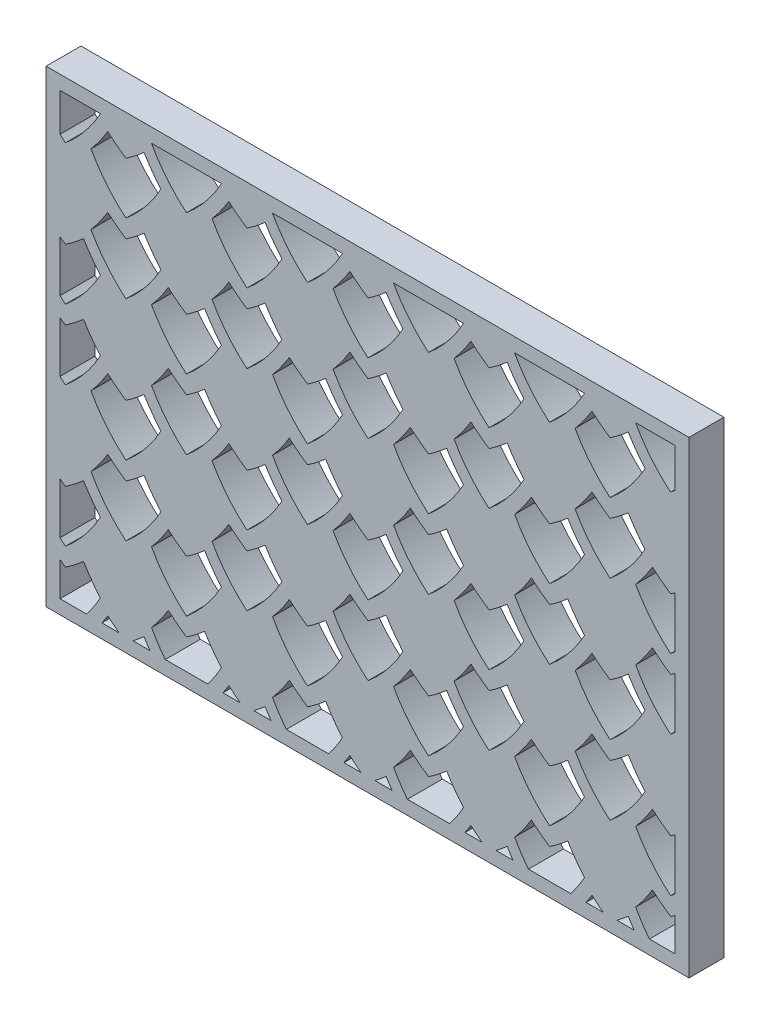
SolidWorks part; units mm, degrees
ref_plane "Front Plane" through (0, 0, 0) normal (0, 0, 1) x (1, 0, 0)
ref_plane "Top Plane" through (0, 0, 0) normal (0, 1, 0) x (1, 0, 0)
ref_plane "Right Plane" through (0, 0, 0) normal (1, 0, 0) x (0, 0, -1)
sketch "Sketch1" plane through (0, 0, 0) normal (0, 0, 1) x (1, 0, 0)
  arc A0 (-49.5966, -68.9633) -> (-54.5966, -62.8719) centre (-35.812, -52.5504) cw
  arc A1 (-54.5966, -62.8719) -> (-52.1907, -59.5393) centre (-73.3761, -46.7798) ccw
  arc A2 (-49.5966, -61.5424) -> (-52.1907, -59.5393) centre (-35.812, -41.0093) cw
  arc A3 (-49.5966, -61.5424) -> (-47.0025, -59.5393) centre (-63.3812, -41.0093) ccw
  arc A4 (-44.5965, -62.8719) -> (-47.0025, -59.5393) centre (-25.8171, -46.7798) cw
  arc A5 (-49.5966, -68.9633) -> (-44.5965, -62.8719) centre (-63.3812, -52.5504) ccw
  arc A6 (-40.9363, -63.9633) -> (-45.9364, -57.8719) centre (-27.1517, -47.5504) cw
  arc A7 (-45.9364, -57.8719) -> (-43.5305, -54.5393) centre (-64.7158, -41.7798) ccw
  arc A8 (-40.9363, -56.5424) -> (-43.5305, -54.5393) centre (-27.1517, -36.0093) cw
  arc A9 (-40.9363, -56.5424) -> (-38.3422, -54.5393) centre (-54.7209, -36.0093) ccw
  arc A10 (-35.9363, -57.8719) -> (-38.3422, -54.5393) centre (-17.1568, -41.7798) cw
  arc A11 (-40.9363, -63.9633) -> (-35.9363, -57.8719) centre (-54.7209, -47.5504) ccw
  arc A12 (-32.2761, -58.9633) -> (-37.2761, -52.8719) centre (-18.4915, -42.5504) cw
  arc A13 (-37.2761, -52.8719) -> (-34.8702, -49.5393) centre (-56.0556, -36.7798) ccw
  arc A14 (-32.2761, -51.5424) -> (-34.8702, -49.5393) centre (-18.4915, -31.0093) cw
  arc A15 (-32.2761, -51.5424) -> (-29.6819, -49.5393) centre (-46.0607, -31.0093) ccw
  arc A16 (-27.276, -52.8719) -> (-29.6819, -49.5393) centre (-8.4966, -36.7798) cw
  arc A17 (-32.2761, -58.9633) -> (-27.276, -52.8719) centre (-46.0607, -42.5504) ccw
  arc A18 (-23.6158, -53.9633) -> (-28.6159, -47.8719) centre (-9.8312, -37.5504) cw
  arc A19 (-28.6159, -47.8719) -> (-26.21, -44.5393) centre (-47.3953, -31.7798) ccw
  arc A20 (-23.6158, -46.5424) -> (-26.21, -44.5393) centre (-9.8312, -26.0093) cw
  arc A21 (-23.6158, -46.5424) -> (-21.0217, -44.5393) centre (-37.4004, -26.0093) ccw
  arc A22 (-18.6158, -47.8719) -> (-21.0217, -44.5393) centre (0.1637, -31.7798) cw
  arc A23 (-23.6158, -53.9633) -> (-18.6158, -47.8719) centre (-37.4004, -37.5504) ccw
  arc A24 (-14.9556, -48.9633) -> (-19.9556, -42.8719) centre (-1.171, -32.5504) cw
  arc A25 (-19.9556, -42.8719) -> (-17.5497, -39.5393) centre (-38.7351, -26.7798) ccw
  arc A26 (-14.9556, -41.5424) -> (-17.5497, -39.5393) centre (-1.171, -21.0093) cw
  arc A27 (-14.9556, -41.5424) -> (-12.3614, -39.5393) centre (-28.7402, -21.0093) ccw
  arc A28 (-9.9555, -42.8719) -> (-12.3614, -39.5393) centre (8.8239, -26.7798) cw
  arc A29 (-14.9556, -48.9633) -> (-9.9555, -42.8719) centre (-28.7402, -32.5504) ccw
  arc A30 (-6.2953, -43.9633) -> (-11.2954, -37.8719) centre (7.4893, -27.5504) cw
  arc A31 (-11.2954, -37.8719) -> (-8.8894, -34.5393) centre (-30.0748, -21.7798) ccw
  arc A32 (-6.2953, -36.5424) -> (-8.8894, -34.5393) centre (7.4893, -16.0093) cw
  arc A33 (-6.2953, -36.5424) -> (-3.7012, -34.5393) centre (-20.0799, -16.0093) ccw
  arc A34 (-1.2953, -37.8719) -> (-3.7012, -34.5393) centre (17.4842, -21.7798) cw
  arc A35 (-6.2953, -43.9633) -> (-1.2953, -37.8719) centre (-20.0799, -27.5504) ccw
  arc A36 (2.3649, -38.9633) -> (-2.6351, -32.8719) centre (16.1495, -22.5504) cw
  arc A37 (-2.6351, -32.8719) -> (-0.2292, -29.5393) centre (-21.4146, -16.7798) ccw
  arc A38 (2.3649, -31.5424) -> (-0.2292, -29.5393) centre (16.1495, -11.0093) cw
  arc A39 (2.3649, -31.5424) -> (4.9591, -29.5393) centre (-11.4196, -11.0093) ccw
  arc A40 (7.365, -32.8719) -> (4.9591, -29.5393) centre (26.1444, -16.7798) cw
  arc A41 (2.3649, -38.9633) -> (7.365, -32.8719) centre (-11.4196, -22.5504) ccw
  arc A42 (11.0252, -33.9633) -> (6.0251, -27.8719) centre (24.8098, -17.5504) cw
  arc A43 (6.0251, -27.8719) -> (8.4311, -24.5393) centre (-12.7543, -11.7798) ccw
  arc A44 (11.0252, -26.5424) -> (8.4311, -24.5393) centre (24.8098, -6.0093) cw
  arc A45 (11.0252, -26.5424) -> (13.6193, -24.5393) centre (-2.7594, -6.0093) ccw
  arc A46 (16.0253, -27.8719) -> (13.6193, -24.5393) centre (34.8047, -11.7798) cw
  arc A47 (11.0252, -33.9633) -> (16.0253, -27.8719) centre (-2.7594, -17.5504) ccw
  arc A54 (28.3457, -23.9633) -> (23.3456, -17.8719) centre (42.1303, -7.5504) cw
  arc A55 (23.3456, -17.8719) -> (25.7516, -14.5393) centre (4.5662, -1.7798) ccw
  arc A56 (28.3457, -16.5424) -> (25.7516, -14.5393) centre (42.1303, 3.9907) cw
  arc A57 (28.3457, -16.5424) -> (30.9398, -14.5393) centre (14.5611, 3.9907) ccw
  arc A58 (33.3458, -17.8719) -> (30.9398, -14.5393) centre (52.1252, -1.7798) cw
  arc A59 (28.3457, -23.9633) -> (33.3458, -17.8719) centre (14.5611, -7.5504) ccw
  arc A60 (37.006, -18.9633) -> (32.0059, -12.8719) centre (50.7905, -2.5504) cw
  arc A61 (32.0059, -12.8719) -> (34.4118, -9.5393) centre (13.2265, 3.2202) ccw
  arc A62 (37.006, -11.5424) -> (34.4118, -9.5393) centre (50.7905, 8.9907) cw
  arc A63 (37.006, -11.5424) -> (39.6001, -9.5393) centre (23.2214, 8.9907) ccw
  arc A64 (42.006, -12.8719) -> (39.6001, -9.5393) centre (60.7855, 3.2202) cw
  arc A65 (37.006, -18.9633) -> (42.006, -12.8719) centre (23.2214, -2.5504) ccw
  arc A66 (-40.9363, -53.9633) -> (-45.9364, -47.8719) centre (-27.1517, -37.5504) cw
  arc A67 (-45.9364, -47.8719) -> (-43.5305, -44.5393) centre (-64.7158, -31.7798) ccw
  arc A68 (-40.9363, -46.5424) -> (-43.5305, -44.5393) centre (-27.1517, -26.0093) cw
  arc A69 (-40.9363, -46.5424) -> (-38.3422, -44.5393) centre (-54.7209, -26.0093) ccw
  arc A70 (-35.9363, -47.8719) -> (-38.3422, -44.5393) centre (-17.1568, -31.7798) cw
  arc A71 (-40.9363, -53.9633) -> (-35.9363, -47.8719) centre (-54.7209, -37.5504) ccw
  arc A72 (-32.2761, -48.9633) -> (-37.2761, -42.8719) centre (-18.4915, -32.5504) cw
  arc A73 (-37.2761, -42.8719) -> (-34.8702, -39.5393) centre (-56.0556, -26.7798) ccw
  arc A74 (-32.2761, -41.5424) -> (-34.8702, -39.5393) centre (-18.4915, -21.0093) cw
  arc A75 (-32.2761, -41.5424) -> (-29.6819, -39.5393) centre (-46.0607, -21.0093) ccw
  arc A76 (-27.276, -42.8719) -> (-29.6819, -39.5393) centre (-8.4966, -26.7798) cw
  arc A77 (-32.2761, -48.9633) -> (-27.276, -42.8719) centre (-46.0607, -32.5504) ccw
  arc A78 (-23.6158, -43.9633) -> (-28.6159, -37.8719) centre (-9.8312, -27.5504) cw
  arc A79 (-28.6159, -37.8719) -> (-26.21, -34.5393) centre (-47.3953, -21.7798) ccw
  arc A80 (-23.6158, -36.5424) -> (-26.21, -34.5393) centre (-9.8312, -16.0093) cw
  arc A81 (-23.6158, -36.5424) -> (-21.0217, -34.5393) centre (-37.4004, -16.0093) ccw
  arc A82 (-18.6158, -37.8719) -> (-21.0217, -34.5393) centre (0.1637, -21.7798) cw
  arc A83 (-23.6158, -43.9633) -> (-18.6158, -37.8719) centre (-37.4004, -27.5504) ccw
  arc A84 (-14.9556, -38.9633) -> (-19.9556, -32.8719) centre (-1.171, -22.5504) cw
  arc A85 (-19.9556, -32.8719) -> (-17.5497, -29.5393) centre (-38.7351, -16.7798) ccw
  arc A86 (-14.9556, -31.5424) -> (-17.5497, -29.5393) centre (-1.171, -11.0093) cw
  arc A87 (-14.9556, -31.5424) -> (-12.3614, -29.5393) centre (-28.7402, -11.0093) ccw
  arc A88 (-9.9555, -32.8719) -> (-12.3614, -29.5393) centre (8.8239, -16.7798) cw
  arc A89 (-14.9556, -38.9633) -> (-9.9555, -32.8719) centre (-28.7402, -22.5504) ccw
  arc A90 (-6.2953, -33.9633) -> (-11.2954, -27.8719) centre (7.4893, -17.5504) cw
  arc A91 (-11.2954, -27.8719) -> (-8.8894, -24.5393) centre (-30.0748, -11.7798) ccw
  arc A92 (-6.2953, -26.5424) -> (-8.8894, -24.5393) centre (7.4893, -6.0093) cw
  arc A93 (-6.2953, -26.5424) -> (-3.7012, -24.5393) centre (-20.0799, -6.0093) ccw
  arc A94 (-1.2953, -27.8719) -> (-3.7012, -24.5393) centre (17.4842, -11.7798) cw
  arc A95 (-6.2953, -33.9633) -> (-1.2953, -27.8719) centre (-20.0799, -17.5504) ccw
  arc A102 (11.0252, -23.9633) -> (6.0251, -17.8719) centre (24.8098, -7.5504) cw
  arc A103 (6.0251, -17.8719) -> (8.4311, -14.5393) centre (-12.7543, -1.7798) ccw
  arc A104 (11.0252, -16.5424) -> (8.4311, -14.5393) centre (24.8098, 3.9907) cw
  arc A105 (11.0252, -16.5424) -> (13.6193, -14.5393) centre (-2.7594, 3.9907) ccw
  arc A106 (16.0253, -17.8719) -> (13.6193, -14.5393) centre (34.8047, -1.7798) cw
  arc A107 (11.0252, -23.9633) -> (16.0253, -17.8719) centre (-2.7594, -7.5504) ccw
  arc A108 (19.6854, -18.9633) -> (14.6854, -12.8719) centre (33.47, -2.5504) cw
  arc A109 (14.6854, -12.8719) -> (17.0913, -9.5393) centre (-4.0941, 3.2202) ccw
  arc A110 (19.6854, -11.5424) -> (17.0913, -9.5393) centre (33.47, 8.9907) cw
  arc A111 (19.6854, -11.5424) -> (22.2796, -9.5393) centre (5.9009, 8.9907) ccw
  arc A112 (24.6855, -12.8719) -> (22.2796, -9.5393) centre (43.4649, 3.2202) cw
  arc A113 (19.6854, -18.9633) -> (24.6855, -12.8719) centre (5.9009, -2.5504) ccw
  arc A120 (37.006, -8.9633) -> (32.0059, -2.8719) centre (50.7905, 7.4496) cw
  arc A121 (32.0059, -2.8719) -> (34.4118, 0.4607) centre (13.2265, 13.2202) ccw
  arc A122 (37.006, -1.5424) -> (34.4118, 0.4607) centre (50.7905, 18.9907) cw
  arc A123 (37.006, -1.5424) -> (39.6001, 0.4607) centre (23.2214, 18.9907) ccw
  arc A124 (42.006, -2.8719) -> (39.6001, 0.4607) centre (60.7855, 13.2202) cw
  arc A125 (37.006, -8.9633) -> (42.006, -2.8719) centre (23.2214, 7.4496) ccw
  arc A126 (-40.9363, -43.9633) -> (-45.9364, -37.8719) centre (-27.1517, -27.5504) cw
  arc A127 (-45.9364, -37.8719) -> (-43.5305, -34.5393) centre (-64.7158, -21.7798) ccw
  arc A128 (-40.9363, -36.5424) -> (-43.5305, -34.5393) centre (-27.1517, -16.0093) cw
  arc A129 (-40.9363, -36.5424) -> (-38.3422, -34.5393) centre (-54.7209, -16.0093) ccw
  arc A130 (-35.9363, -37.8719) -> (-38.3422, -34.5393) centre (-17.1568, -21.7798) cw
  arc A131 (-40.9363, -43.9633) -> (-35.9363, -37.8719) centre (-54.7209, -27.5504) ccw
  arc A132 (-32.2761, -38.9633) -> (-37.2761, -32.8719) centre (-18.4915, -22.5504) cw
  arc A133 (-37.2761, -32.8719) -> (-34.8702, -29.5393) centre (-56.0556, -16.7798) ccw
  arc A134 (-32.2761, -31.5424) -> (-34.8702, -29.5393) centre (-18.4915, -11.0093) cw
  arc A135 (-32.2761, -31.5424) -> (-29.6819, -29.5393) centre (-46.0607, -11.0093) ccw
  arc A136 (-27.276, -32.8719) -> (-29.6819, -29.5393) centre (-8.4966, -16.7798) cw
  arc A137 (-32.2761, -38.9633) -> (-27.276, -32.8719) centre (-46.0607, -22.5504) ccw
  arc A138 (-23.6158, -33.9633) -> (-28.6159, -27.8719) centre (-9.8312, -17.5504) cw
  arc A139 (-28.6159, -27.8719) -> (-26.21, -24.5393) centre (-47.3953, -11.7798) ccw
  arc A140 (-23.6158, -26.5424) -> (-26.21, -24.5393) centre (-9.8312, -6.0093) cw
  arc A141 (-23.6158, -26.5424) -> (-21.0217, -24.5393) centre (-37.4004, -6.0093) ccw
  arc A142 (-18.6158, -27.8719) -> (-21.0217, -24.5393) centre (0.1637, -11.7798) cw
  arc A143 (-23.6158, -33.9633) -> (-18.6158, -27.8719) centre (-37.4004, -17.5504) ccw
  arc A150 (-6.2953, -23.9633) -> (-11.2954, -17.8719) centre (7.4893, -7.5504) cw
  arc A151 (-11.2954, -17.8719) -> (-8.8894, -14.5393) centre (-30.0748, -1.7798) ccw
  arc A152 (-6.2953, -16.5424) -> (-8.8894, -14.5393) centre (7.4893, 3.9907) cw
  arc A153 (-6.2953, -16.5424) -> (-3.7012, -14.5393) centre (-20.0799, 3.9907) ccw
  arc A154 (-1.2953, -17.8719) -> (-3.7012, -14.5393) centre (17.4842, -1.7798) cw
  arc A155 (-6.2953, -23.9633) -> (-1.2953, -17.8719) centre (-20.0799, -7.5504) ccw
  arc A156 (2.3649, -18.9633) -> (-2.6351, -12.8719) centre (16.1495, -2.5504) cw
  arc A157 (-2.6351, -12.8719) -> (-0.2292, -9.5393) centre (-21.4146, 3.2202) ccw
  arc A158 (2.3649, -11.5424) -> (-0.2292, -9.5393) centre (16.1495, 8.9907) cw
  arc A159 (2.3649, -11.5424) -> (4.9591, -9.5393) centre (-11.4196, 8.9907) ccw
  arc A160 (7.365, -12.8719) -> (4.9591, -9.5393) centre (26.1444, 3.2202) cw
  arc A161 (2.3649, -18.9633) -> (7.365, -12.8719) centre (-11.4196, -2.5504) ccw
  arc A168 (19.6854, -8.9633) -> (14.6854, -2.8719) centre (33.47, 7.4496) cw
  arc A169 (14.6854, -2.8719) -> (17.0913, 0.4607) centre (-4.0941, 13.2202) ccw
  arc A170 (19.6854, -1.5424) -> (17.0913, 0.4607) centre (33.47, 18.9907) cw
  arc A171 (19.6854, -1.5424) -> (22.2796, 0.4607) centre (5.9009, 18.9907) ccw
  arc A172 (24.6855, -2.8719) -> (22.2796, 0.4607) centre (43.4649, 13.2202) cw
  arc A173 (19.6854, -8.9633) -> (24.6855, -2.8719) centre (5.9009, 7.4496) ccw
  arc A174 (28.3457, -3.9633) -> (23.3456, 2.1281) centre (42.1303, 12.4496) cw
  arc A175 (23.3456, 2.1281) -> (25.7516, 5.4607) centre (4.5662, 18.2202) ccw
  arc A176 (28.3457, 3.4576) -> (25.7516, 5.4607) centre (42.1303, 23.9907) cw
  arc A177 (28.3457, 3.4576) -> (30.9398, 5.4607) centre (14.5611, 23.9907) ccw
  arc A178 (33.3458, 2.1281) -> (30.9398, 5.4607) centre (52.1252, 18.2202) cw
  arc A179 (28.3457, -3.9633) -> (33.3458, 2.1281) centre (14.5611, 12.4496) ccw
  arc A186 (-40.9363, -33.9633) -> (-45.9364, -27.8719) centre (-27.1517, -17.5504) cw
  arc A187 (-45.9364, -27.8719) -> (-43.5305, -24.5393) centre (-64.7158, -11.7798) ccw
  arc A188 (-40.9363, -26.5424) -> (-43.5305, -24.5393) centre (-27.1517, -6.0093) cw
  arc A189 (-40.9363, -26.5424) -> (-38.3422, -24.5393) centre (-54.7209, -6.0093) ccw
  arc A190 (-35.9363, -27.8719) -> (-38.3422, -24.5393) centre (-17.1568, -11.7798) cw
  arc A191 (-40.9363, -33.9633) -> (-35.9363, -27.8719) centre (-54.7209, -17.5504) ccw
  arc A198 (-23.6158, -23.9633) -> (-28.6159, -17.8719) centre (-9.8312, -7.5504) cw
  arc A199 (-28.6159, -17.8719) -> (-26.21, -14.5393) centre (-47.3953, -1.7798) ccw
  arc A200 (-23.6158, -16.5424) -> (-26.21, -14.5393) centre (-9.8312, 3.9907) cw
  arc A201 (-23.6158, -16.5424) -> (-21.0217, -14.5393) centre (-37.4004, 3.9907) ccw
  arc A202 (-18.6158, -17.8719) -> (-21.0217, -14.5393) centre (0.1637, -1.7798) cw
  arc A203 (-23.6158, -23.9633) -> (-18.6158, -17.8719) centre (-37.4004, -7.5504) ccw
  arc A204 (-14.9556, -18.9633) -> (-19.9556, -12.8719) centre (-1.171, -2.5504) cw
  arc A205 (-19.9556, -12.8719) -> (-17.5497, -9.5393) centre (-38.7351, 3.2202) ccw
  arc A206 (-14.9556, -11.5424) -> (-17.5497, -9.5393) centre (-1.171, 8.9907) cw
  arc A207 (-14.9556, -11.5424) -> (-12.3614, -9.5393) centre (-28.7402, 8.9907) ccw
  arc A208 (-9.9555, -12.8719) -> (-12.3614, -9.5393) centre (8.8239, 3.2202) cw
  arc A209 (-14.9556, -18.9633) -> (-9.9555, -12.8719) centre (-28.7402, -2.5504) ccw
  arc A216 (2.3649, -8.9633) -> (-2.6351, -2.8719) centre (16.1495, 7.4496) cw
  arc A217 (-2.6351, -2.8719) -> (-0.2292, 0.4607) centre (-21.4146, 13.2202) ccw
  arc A218 (2.3649, -1.5424) -> (-0.2292, 0.4607) centre (16.1495, 18.9907) cw
  arc A219 (2.3649, -1.5424) -> (4.9591, 0.4607) centre (-11.4196, 18.9907) ccw
  arc A220 (7.365, -2.8719) -> (4.9591, 0.4607) centre (26.1444, 13.2202) cw
  arc A221 (2.3649, -8.9633) -> (7.365, -2.8719) centre (-11.4196, 7.4496) ccw
  arc A222 (11.0252, -3.9633) -> (6.0251, 2.1281) centre (24.8098, 12.4496) cw
  arc A223 (6.0251, 2.1281) -> (8.4311, 5.4607) centre (-12.7543, 18.2202) ccw
  arc A224 (11.0252, 3.4576) -> (8.4311, 5.4607) centre (24.8098, 23.9907) cw
  arc A225 (11.0252, 3.4576) -> (13.6193, 5.4607) centre (-2.7594, 23.9907) ccw
  arc A226 (16.0253, 2.1281) -> (13.6193, 5.4607) centre (34.8047, 18.2202) cw
  arc A227 (11.0252, -3.9633) -> (16.0253, 2.1281) centre (-2.7594, 12.4496) ccw
  arc A234 (28.3457, 6.0367) -> (23.3456, 12.1281) centre (42.1303, 22.4496) cw
  arc A235 (23.3456, 12.1281) -> (25.7516, 15.4607) centre (4.5662, 28.2202) ccw
  arc A236 (28.3457, 13.4576) -> (25.7516, 15.4607) centre (42.1303, 33.9907) cw
  arc A237 (28.3457, 13.4576) -> (30.9398, 15.4607) centre (14.5611, 33.9907) ccw
  arc A238 (33.3458, 12.1281) -> (30.9398, 15.4607) centre (52.1252, 28.2202) cw
  arc A239 (28.3457, 6.0367) -> (33.3458, 12.1281) centre (14.5611, 22.4496) ccw
  arc A240 (37.006, 11.0367) -> (32.0059, 17.1281) centre (50.7905, 27.4496) cw
  arc A241 (32.0059, 17.1281) -> (34.4118, 20.4607) centre (13.2265, 33.2202) ccw
  arc A242 (37.006, 18.4576) -> (34.4118, 20.4607) centre (50.7905, 38.9907) cw
  arc A243 (37.006, 18.4576) -> (39.6001, 20.4607) centre (23.2214, 38.9907) ccw
  arc A244 (42.006, 17.1281) -> (39.6001, 20.4607) centre (60.7855, 33.2202) cw
  arc A245 (37.006, 11.0367) -> (42.006, 17.1281) centre (23.2214, 27.4496) ccw
  arc A246 (-40.9363, -23.9633) -> (-45.9364, -17.8719) centre (-27.1517, -7.5504) cw
  arc A247 (-45.9364, -17.8719) -> (-43.5305, -14.5393) centre (-64.7158, -1.7798) ccw
  arc A248 (-40.9363, -16.5424) -> (-43.5305, -14.5393) centre (-27.1517, 3.9907) cw
  arc A249 (-40.9363, -16.5424) -> (-38.3422, -14.5393) centre (-54.7209, 3.9907) ccw
  arc A250 (-35.9363, -17.8719) -> (-38.3422, -14.5393) centre (-17.1568, -1.7798) cw
  arc A251 (-40.9363, -23.9633) -> (-35.9363, -17.8719) centre (-54.7209, -7.5504) ccw
  arc A252 (-32.2761, -18.9633) -> (-37.2761, -12.8719) centre (-18.4915, -2.5504) cw
  arc A253 (-37.2761, -12.8719) -> (-34.8702, -9.5393) centre (-56.0556, 3.2202) ccw
  arc A254 (-32.2761, -11.5424) -> (-34.8702, -9.5393) centre (-18.4915, 8.9907) cw
  arc A255 (-32.2761, -11.5424) -> (-29.6819, -9.5393) centre (-46.0607, 8.9907) ccw
  arc A256 (-27.276, -12.8719) -> (-29.6819, -9.5393) centre (-8.4966, 3.2202) cw
  arc A257 (-32.2761, -18.9633) -> (-27.276, -12.8719) centre (-46.0607, -2.5504) ccw
  arc A264 (-14.9556, -8.9633) -> (-19.9556, -2.8719) centre (-1.171, 7.4496) cw
  arc A265 (-19.9556, -2.8719) -> (-17.5497, 0.4607) centre (-38.7351, 13.2202) ccw
  arc A266 (-14.9556, -1.5424) -> (-17.5497, 0.4607) centre (-1.171, 18.9907) cw
  arc A267 (-14.9556, -1.5424) -> (-12.3614, 0.4607) centre (-28.7402, 18.9907) ccw
  arc A268 (-9.9555, -2.8719) -> (-12.3614, 0.4607) centre (8.8239, 13.2202) cw
  arc A269 (-14.9556, -8.9633) -> (-9.9555, -2.8719) centre (-28.7402, 7.4496) ccw
  arc A270 (-6.2953, -3.9633) -> (-11.2954, 2.1281) centre (7.4893, 12.4496) cw
  arc A271 (-11.2954, 2.1281) -> (-8.8894, 5.4607) centre (-30.0748, 18.2202) ccw
  arc A272 (-6.2953, 3.4576) -> (-8.8894, 5.4607) centre (7.4893, 23.9907) cw
  arc A273 (-6.2953, 3.4576) -> (-3.7012, 5.4607) centre (-20.0799, 23.9907) ccw
  arc A274 (-1.2953, 2.1281) -> (-3.7012, 5.4607) centre (17.4842, 18.2202) cw
  arc A275 (-6.2953, -3.9633) -> (-1.2953, 2.1281) centre (-20.0799, 12.4496) ccw
  arc A282 (11.0252, 6.0367) -> (6.0251, 12.1281) centre (24.8098, 22.4496) cw
  arc A283 (6.0251, 12.1281) -> (8.4311, 15.4607) centre (-12.7543, 28.2202) ccw
  arc A284 (11.0252, 13.4576) -> (8.4311, 15.4607) centre (24.8098, 33.9907) cw
  arc A285 (11.0252, 13.4576) -> (13.6193, 15.4607) centre (-2.7594, 33.9907) ccw
  arc A286 (16.0253, 12.1281) -> (13.6193, 15.4607) centre (34.8047, 28.2202) cw
  arc A287 (11.0252, 6.0367) -> (16.0253, 12.1281) centre (-2.7594, 22.4496) ccw
  arc A288 (19.6854, 11.0367) -> (14.6854, 17.1281) centre (33.47, 27.4496) cw
  arc A289 (14.6854, 17.1281) -> (17.0913, 20.4607) centre (-4.0941, 33.2202) ccw
  arc A290 (19.6854, 18.4576) -> (17.0913, 20.4607) centre (33.47, 38.9907) cw
  arc A291 (19.6854, 18.4576) -> (22.2796, 20.4607) centre (5.9009, 38.9907) ccw
  arc A292 (24.6855, 17.1281) -> (22.2796, 20.4607) centre (43.4649, 33.2202) cw
  arc A293 (19.6854, 11.0367) -> (24.6855, 17.1281) centre (5.9009, 27.4496) ccw
  arc A300 (37.006, 21.0367) -> (32.0059, 27.1281) centre (50.7905, 37.4496) cw
  arc A301 (32.0059, 27.1281) -> (34.4118, 30.4607) centre (13.2265, 43.2202) ccw
  arc A302 (37.006, 28.4576) -> (34.4118, 30.4607) centre (50.7905, 48.9907) cw
  arc A303 (37.006, 28.4576) -> (39.6001, 30.4607) centre (23.2214, 48.9907) ccw
  arc A304 (42.006, 27.1281) -> (39.6001, 30.4607) centre (60.7855, 43.2202) cw
  arc A305 (37.006, 21.0367) -> (42.006, 27.1281) centre (23.2214, 37.4496) ccw
  arc A312 (-32.2761, -8.9633) -> (-37.2761, -2.8719) centre (-18.4915, 7.4496) cw
  arc A313 (-37.2761, -2.8719) -> (-34.8702, 0.4607) centre (-56.0556, 13.2202) ccw
  arc A314 (-32.2761, -1.5424) -> (-34.8702, 0.4607) centre (-18.4915, 18.9907) cw
  arc A315 (-32.2761, -1.5424) -> (-29.6819, 0.4607) centre (-46.0607, 18.9907) ccw
  arc A316 (-27.276, -2.8719) -> (-29.6819, 0.4607) centre (-8.4966, 13.2202) cw
  arc A317 (-32.2761, -8.9633) -> (-27.276, -2.8719) centre (-46.0607, 7.4496) ccw
  arc A318 (-23.6158, -3.9633) -> (-28.6159, 2.1281) centre (-9.8312, 12.4496) cw
  arc A319 (-28.6159, 2.1281) -> (-26.21, 5.4607) centre (-47.3953, 18.2202) ccw
  arc A320 (-23.6158, 3.4576) -> (-26.21, 5.4607) centre (-9.8312, 23.9907) cw
  arc A321 (-23.6158, 3.4576) -> (-21.0217, 5.4607) centre (-37.4004, 23.9907) ccw
  arc A322 (-18.6158, 2.1281) -> (-21.0217, 5.4607) centre (0.1637, 18.2202) cw
  arc A323 (-23.6158, -3.9633) -> (-18.6158, 2.1281) centre (-37.4004, 12.4496) ccw
  arc A330 (-6.2953, 6.0367) -> (-11.2954, 12.1281) centre (7.4893, 22.4496) cw
  arc A331 (-11.2954, 12.1281) -> (-8.8894, 15.4607) centre (-30.0748, 28.2202) ccw
  arc A332 (-6.2953, 13.4576) -> (-8.8894, 15.4607) centre (7.4893, 33.9907) cw
  arc A333 (-6.2953, 13.4576) -> (-3.7012, 15.4607) centre (-20.0799, 33.9907) ccw
  arc A334 (-1.2953, 12.1281) -> (-3.7012, 15.4607) centre (17.4842, 28.2202) cw
  arc A335 (-6.2953, 6.0367) -> (-1.2953, 12.1281) centre (-20.0799, 22.4496) ccw
  arc A336 (2.3649, 11.0367) -> (-2.6351, 17.1281) centre (16.1495, 27.4496) cw
  arc A337 (-2.6351, 17.1281) -> (-0.2292, 20.4607) centre (-21.4146, 33.2202) ccw
  arc A338 (2.3649, 18.4576) -> (-0.2292, 20.4607) centre (16.1495, 38.9907) cw
  arc A339 (2.3649, 18.4576) -> (4.9591, 20.4607) centre (-11.4196, 38.9907) ccw
  arc A340 (7.365, 17.1281) -> (4.9591, 20.4607) centre (26.1444, 33.2202) cw
  arc A341 (2.3649, 11.0367) -> (7.365, 17.1281) centre (-11.4196, 27.4496) ccw
  arc A348 (19.6854, 21.0367) -> (14.6854, 27.1281) centre (33.47, 37.4496) cw
  arc A349 (14.6854, 27.1281) -> (17.0913, 30.4607) centre (-4.0941, 43.2202) ccw
  arc A350 (19.6854, 28.4576) -> (17.0913, 30.4607) centre (33.47, 48.9907) cw
  arc A351 (19.6854, 28.4576) -> (22.2796, 30.4607) centre (5.9009, 48.9907) ccw
  arc A352 (24.6855, 27.1281) -> (22.2796, 30.4607) centre (43.4649, 43.2202) cw
  arc A353 (19.6854, 21.0367) -> (24.6855, 27.1281) centre (5.9009, 37.4496) ccw
  arc A354 (28.3457, 26.0367) -> (23.3456, 32.1281) centre (42.1303, 42.4496) cw
  arc A355 (23.3456, 32.1281) -> (25.7516, 35.4607) centre (4.5662, 48.2202) ccw
  arc A356 (28.3457, 33.4576) -> (25.7516, 35.4607) centre (42.1303, 53.9907) cw
  arc A357 (28.3457, 33.4576) -> (30.9398, 35.4607) centre (14.5611, 53.9907) ccw
  arc A358 (33.3458, 32.1281) -> (30.9398, 35.4607) centre (52.1252, 48.2202) cw
  arc A359 (28.3457, 26.0367) -> (33.3458, 32.1281) centre (14.5611, 42.4496) ccw
  arc A366 (-40.9363, -3.9633) -> (-45.9364, 2.1281) centre (-27.1517, 12.4496) cw
  arc A367 (-45.9364, 2.1281) -> (-43.5305, 5.4607) centre (-64.7158, 18.2202) ccw
  arc A368 (-40.9363, 3.4576) -> (-43.5305, 5.4607) centre (-27.1517, 23.9907) cw
  arc A369 (-40.9363, 3.4576) -> (-38.3422, 5.4607) centre (-54.7209, 23.9907) ccw
  arc A370 (-35.9363, 2.1281) -> (-38.3422, 5.4607) centre (-17.1568, 18.2202) cw
  arc A371 (-40.9363, -3.9633) -> (-35.9363, 2.1281) centre (-54.7209, 12.4496) ccw
  arc A378 (-23.6158, 6.0367) -> (-28.6159, 12.1281) centre (-9.8312, 22.4496) cw
  arc A379 (-28.6159, 12.1281) -> (-26.21, 15.4607) centre (-47.3953, 28.2202) ccw
  arc A380 (-23.6158, 13.4576) -> (-26.21, 15.4607) centre (-9.8312, 33.9907) cw
  arc A381 (-23.6158, 13.4576) -> (-21.0217, 15.4607) centre (-37.4004, 33.9907) ccw
  arc A382 (-18.6158, 12.1281) -> (-21.0217, 15.4607) centre (0.1637, 28.2202) cw
  arc A383 (-23.6158, 6.0367) -> (-18.6158, 12.1281) centre (-37.4004, 22.4496) ccw
  arc A384 (-14.9556, 11.0367) -> (-19.9556, 17.1281) centre (-1.171, 27.4496) cw
  arc A385 (-19.9556, 17.1281) -> (-17.5497, 20.4607) centre (-38.7351, 33.2202) ccw
  arc A386 (-14.9556, 18.4576) -> (-17.5497, 20.4607) centre (-1.171, 38.9907) cw
  arc A387 (-14.9556, 18.4576) -> (-12.3614, 20.4607) centre (-28.7402, 38.9907) ccw
  arc A388 (-9.9555, 17.1281) -> (-12.3614, 20.4607) centre (8.8239, 33.2202) cw
  arc A389 (-14.9556, 11.0367) -> (-9.9555, 17.1281) centre (-28.7402, 27.4496) ccw
  arc A396 (2.3649, 21.0367) -> (-2.6351, 27.1281) centre (16.1495, 37.4496) cw
  arc A397 (-2.6351, 27.1281) -> (-0.2292, 30.4607) centre (-21.4146, 43.2202) ccw
  arc A398 (2.3649, 28.4576) -> (-0.2292, 30.4607) centre (16.1495, 48.9907) cw
  arc A399 (2.3649, 28.4576) -> (4.9591, 30.4607) centre (-11.4196, 48.9907) ccw
  arc A400 (7.365, 27.1281) -> (4.9591, 30.4607) centre (26.1444, 43.2202) cw
  arc A401 (2.3649, 21.0367) -> (7.365, 27.1281) centre (-11.4196, 37.4496) ccw
  arc A402 (11.0252, 26.0367) -> (6.0251, 32.1281) centre (24.8098, 42.4496) cw
  arc A403 (6.0251, 32.1281) -> (8.4311, 35.4607) centre (-12.7543, 48.2202) ccw
  arc A404 (11.0252, 33.4576) -> (8.4311, 35.4607) centre (24.8098, 53.9907) cw
  arc A405 (11.0252, 33.4576) -> (13.6193, 35.4607) centre (-2.7594, 53.9907) ccw
  arc A406 (16.0253, 32.1281) -> (13.6193, 35.4607) centre (34.8047, 48.2202) cw
  arc A407 (11.0252, 26.0367) -> (16.0253, 32.1281) centre (-2.7594, 42.4496) ccw
  arc A414 (28.3457, 36.0367) -> (23.3456, 42.1281) centre (42.1303, 52.4496) cw
  arc A415 (23.3456, 42.1281) -> (25.7516, 45.4607) centre (4.5662, 58.2202) ccw
  arc A416 (28.3457, 43.4576) -> (25.7516, 45.4607) centre (42.1303, 63.9907) cw
  arc A417 (28.3457, 43.4576) -> (30.9398, 45.4607) centre (14.5611, 63.9907) ccw
  arc A418 (33.3458, 42.1281) -> (30.9398, 45.4607) centre (52.1252, 58.2202) cw
  arc A419 (28.3457, 36.0367) -> (33.3458, 42.1281) centre (14.5611, 52.4496) ccw
  arc A420 (37.006, 41.0367) -> (32.0059, 47.1281) centre (50.7905, 57.4496) cw
  arc A421 (32.0059, 47.1281) -> (34.4118, 50.4607) centre (13.2265, 63.2202) ccw
  arc A422 (37.006, 48.4576) -> (34.4118, 50.4607) centre (50.7905, 68.9907) cw
  arc A423 (37.006, 48.4576) -> (39.6001, 50.4607) centre (23.2214, 68.9907) ccw
  arc A424 (42.006, 47.1281) -> (39.6001, 50.4607) centre (60.7855, 63.2202) cw
  arc A425 (37.006, 41.0367) -> (42.006, 47.1281) centre (23.2214, 57.4496) ccw
  arc A426 (-40.9363, 6.0367) -> (-45.9364, 12.1281) centre (-27.1517, 22.4496) cw
  arc A427 (-45.9364, 12.1281) -> (-43.5305, 15.4607) centre (-64.7158, 28.2202) ccw
  arc A428 (-40.9363, 13.4576) -> (-43.5305, 15.4607) centre (-27.1517, 33.9907) cw
  arc A429 (-40.9363, 13.4576) -> (-38.3422, 15.4607) centre (-54.7209, 33.9907) ccw
  arc A430 (-35.9363, 12.1281) -> (-38.3422, 15.4607) centre (-17.1568, 28.2202) cw
  arc A431 (-40.9363, 6.0367) -> (-35.9363, 12.1281) centre (-54.7209, 22.4496) ccw
  arc A432 (-32.2761, 11.0367) -> (-37.2761, 17.1281) centre (-18.4915, 27.4496) cw
  arc A433 (-37.2761, 17.1281) -> (-34.8702, 20.4607) centre (-56.0556, 33.2202) ccw
  arc A434 (-32.2761, 18.4576) -> (-34.8702, 20.4607) centre (-18.4915, 38.9907) cw
  arc A435 (-32.2761, 18.4576) -> (-29.6819, 20.4607) centre (-46.0607, 38.9907) ccw
  arc A436 (-27.276, 17.1281) -> (-29.6819, 20.4607) centre (-8.4966, 33.2202) cw
  arc A437 (-32.2761, 11.0367) -> (-27.276, 17.1281) centre (-46.0607, 27.4496) ccw
  arc A444 (-14.9556, 21.0367) -> (-19.9556, 27.1281) centre (-1.171, 37.4496) cw
  arc A445 (-19.9556, 27.1281) -> (-17.5497, 30.4607) centre (-38.7351, 43.2202) ccw
  arc A446 (-14.9556, 28.4576) -> (-17.5497, 30.4607) centre (-1.171, 48.9907) cw
  arc A447 (-14.9556, 28.4576) -> (-12.3614, 30.4607) centre (-28.7402, 48.9907) ccw
  arc A448 (-9.9555, 27.1281) -> (-12.3614, 30.4607) centre (8.8239, 43.2202) cw
  arc A449 (-14.9556, 21.0367) -> (-9.9555, 27.1281) centre (-28.7402, 37.4496) ccw
  arc A450 (-6.2953, 26.0367) -> (-11.2954, 32.1281) centre (7.4893, 42.4496) cw
  arc A451 (-11.2954, 32.1281) -> (-8.8894, 35.4607) centre (-30.0748, 48.2202) ccw
  arc A452 (-6.2953, 33.4576) -> (-8.8894, 35.4607) centre (7.4893, 53.9907) cw
  arc A453 (-6.2953, 33.4576) -> (-3.7012, 35.4607) centre (-20.0799, 53.9907) ccw
  arc A454 (-1.2953, 32.1281) -> (-3.7012, 35.4607) centre (17.4842, 48.2202) cw
  arc A455 (-6.2953, 26.0367) -> (-1.2953, 32.1281) centre (-20.0799, 42.4496) ccw
  arc A462 (11.0252, 36.0367) -> (6.0251, 42.1281) centre (24.8098, 52.4496) cw
  arc A463 (6.0251, 42.1281) -> (8.4311, 45.4607) centre (-12.7543, 58.2202) ccw
  arc A464 (11.0252, 43.4576) -> (8.4311, 45.4607) centre (24.8098, 63.9907) cw
  arc A465 (11.0252, 43.4576) -> (13.6193, 45.4607) centre (-2.7594, 63.9907) ccw
  arc A466 (16.0253, 42.1281) -> (13.6193, 45.4607) centre (34.8047, 58.2202) cw
  arc A467 (11.0252, 36.0367) -> (16.0253, 42.1281) centre (-2.7594, 52.4496) ccw
  arc A468 (19.6854, 41.0367) -> (14.6854, 47.1281) centre (33.47, 57.4496) cw
  arc A469 (14.6854, 47.1281) -> (17.0913, 50.4607) centre (-4.0941, 63.2202) ccw
  arc A470 (19.6854, 48.4576) -> (17.0913, 50.4607) centre (33.47, 68.9907) cw
  arc A471 (19.6854, 48.4576) -> (22.2796, 50.4607) centre (5.9009, 68.9907) ccw
  arc A472 (24.6855, 47.1281) -> (22.2796, 50.4607) centre (43.4649, 63.2202) cw
  arc A473 (19.6854, 41.0367) -> (24.6855, 47.1281) centre (5.9009, 57.4496) ccw
  arc A480 (37.006, 51.0367) -> (32.0059, 57.1281) centre (50.7905, 67.4496) cw
  arc A481 (32.0059, 57.1281) -> (34.4118, 60.4607) centre (13.2265, 73.2202) ccw
  arc A482 (37.006, 58.4576) -> (34.4118, 60.4607) centre (50.7905, 78.9907) cw
  arc A483 (37.006, 58.4576) -> (39.6001, 60.4607) centre (23.2214, 78.9907) ccw
  arc A484 (42.006, 57.1281) -> (39.6001, 60.4607) centre (60.7855, 73.2202) cw
  arc A485 (37.006, 51.0367) -> (42.006, 57.1281) centre (23.2214, 67.4496) ccw
  arc A492 (-32.2761, 21.0367) -> (-37.2761, 27.1281) centre (-18.4915, 37.4496) cw
  arc A493 (-37.2761, 27.1281) -> (-34.8702, 30.4607) centre (-56.0556, 43.2202) ccw
  arc A494 (-32.2761, 28.4576) -> (-34.8702, 30.4607) centre (-18.4915, 48.9907) cw
  arc A495 (-32.2761, 28.4576) -> (-29.6819, 30.4607) centre (-46.0607, 48.9907) ccw
  arc A496 (-27.276, 27.1281) -> (-29.6819, 30.4607) centre (-8.4966, 43.2202) cw
  arc A497 (-32.2761, 21.0367) -> (-27.276, 27.1281) centre (-46.0607, 37.4496) ccw
  arc A498 (-23.6158, 26.0367) -> (-28.6159, 32.1281) centre (-9.8312, 42.4496) cw
  arc A499 (-28.6159, 32.1281) -> (-26.21, 35.4607) centre (-47.3953, 48.2202) ccw
  arc A500 (-23.6158, 33.4576) -> (-26.21, 35.4607) centre (-9.8312, 53.9907) cw
  arc A501 (-23.6158, 33.4576) -> (-21.0217, 35.4607) centre (-37.4004, 53.9907) ccw
  arc A502 (-18.6158, 32.1281) -> (-21.0217, 35.4607) centre (0.1637, 48.2202) cw
  arc A503 (-23.6158, 26.0367) -> (-18.6158, 32.1281) centre (-37.4004, 42.4496) ccw
  arc A510 (-6.2953, 36.0367) -> (-11.2954, 42.1281) centre (7.4893, 52.4496) cw
  arc A511 (-11.2954, 42.1281) -> (-8.8894, 45.4607) centre (-30.0748, 58.2202) ccw
  arc A512 (-6.2953, 43.4576) -> (-8.8894, 45.4607) centre (7.4893, 63.9907) cw
  arc A513 (-6.2953, 43.4576) -> (-3.7012, 45.4607) centre (-20.0799, 63.9907) ccw
  arc A514 (-1.2953, 42.1281) -> (-3.7012, 45.4607) centre (17.4842, 58.2202) cw
  arc A515 (-6.2953, 36.0367) -> (-1.2953, 42.1281) centre (-20.0799, 52.4496) ccw
  arc A516 (2.3649, 41.0367) -> (-2.6351, 47.1281) centre (16.1495, 57.4496) cw
  arc A517 (-2.6351, 47.1281) -> (-0.2292, 50.4607) centre (-21.4146, 63.2202) ccw
  arc A518 (2.3649, 48.4576) -> (-0.2292, 50.4607) centre (16.1495, 68.9907) cw
  arc A519 (2.3649, 48.4576) -> (4.9591, 50.4607) centre (-11.4196, 68.9907) ccw
  arc A520 (7.365, 47.1281) -> (4.9591, 50.4607) centre (26.1444, 63.2202) cw
  arc A521 (2.3649, 41.0367) -> (7.365, 47.1281) centre (-11.4196, 57.4496) ccw
  arc A528 (19.6854, 51.0367) -> (14.6854, 57.1281) centre (33.47, 67.4496) cw
  arc A529 (14.6854, 57.1281) -> (17.0913, 60.4607) centre (-4.0941, 73.2202) ccw
  arc A530 (19.6854, 58.4576) -> (17.0913, 60.4607) centre (33.47, 78.9907) cw
  arc A531 (19.6854, 58.4576) -> (22.2796, 60.4607) centre (5.9009, 78.9907) ccw
  arc A532 (24.6855, 57.1281) -> (22.2796, 60.4607) centre (43.4649, 73.2202) cw
  arc A533 (19.6854, 51.0367) -> (24.6855, 57.1281) centre (5.9009, 67.4496) ccw
  arc A534 (28.3457, 56.0367) -> (23.3456, 62.1281) centre (42.1303, 72.4496) cw
  arc A535 (23.3456, 62.1281) -> (25.7516, 65.4607) centre (4.5662, 78.2202) ccw
  arc A536 (28.3457, 63.4576) -> (25.7516, 65.4607) centre (42.1303, 83.9907) cw
  arc A537 (28.3457, 63.4576) -> (30.9398, 65.4607) centre (14.5611, 83.9907) ccw
  arc A538 (33.3458, 62.1281) -> (30.9398, 65.4607) centre (52.1252, 78.2202) cw
  arc A539 (28.3457, 56.0367) -> (33.3458, 62.1281) centre (14.5611, 72.4496) ccw
  arc A546 (-40.9363, 26.0367) -> (-45.9364, 32.1281) centre (-27.1517, 42.4496) cw
  arc A547 (-45.9364, 32.1281) -> (-43.5305, 35.4607) centre (-64.7158, 48.2202) ccw
  arc A548 (-40.9363, 33.4576) -> (-43.5305, 35.4607) centre (-27.1517, 53.9907) cw
  arc A549 (-40.9363, 33.4576) -> (-38.3422, 35.4607) centre (-54.7209, 53.9907) ccw
  arc A550 (-35.9363, 32.1281) -> (-38.3422, 35.4607) centre (-17.1568, 48.2202) cw
  arc A551 (-40.9363, 26.0367) -> (-35.9363, 32.1281) centre (-54.7209, 42.4496) ccw
  arc A558 (-23.6158, 36.0367) -> (-28.6159, 42.1281) centre (-9.8312, 52.4496) cw
  arc A559 (-28.6159, 42.1281) -> (-26.21, 45.4607) centre (-47.3953, 58.2202) ccw
  arc A560 (-23.6158, 43.4576) -> (-26.21, 45.4607) centre (-9.8312, 63.9907) cw
  arc A561 (-23.6158, 43.4576) -> (-21.0217, 45.4607) centre (-37.4004, 63.9907) ccw
  arc A562 (-18.6158, 42.1281) -> (-21.0217, 45.4607) centre (0.1637, 58.2202) cw
  arc A563 (-23.6158, 36.0367) -> (-18.6158, 42.1281) centre (-37.4004, 52.4496) ccw
  arc A564 (-14.9556, 41.0367) -> (-19.9556, 47.1281) centre (-1.171, 57.4496) cw
  arc A565 (-19.9556, 47.1281) -> (-17.5497, 50.4607) centre (-38.7351, 63.2202) ccw
  arc A566 (-14.9556, 48.4576) -> (-17.5497, 50.4607) centre (-1.171, 68.9907) cw
  arc A567 (-14.9556, 48.4576) -> (-12.3614, 50.4607) centre (-28.7402, 68.9907) ccw
  arc A568 (-9.9555, 47.1281) -> (-12.3614, 50.4607) centre (8.8239, 63.2202) cw
  arc A569 (-14.9556, 41.0367) -> (-9.9555, 47.1281) centre (-28.7402, 57.4496) ccw
  arc A576 (2.3649, 51.0367) -> (-2.6351, 57.1281) centre (16.1495, 67.4496) cw
  arc A577 (-2.6351, 57.1281) -> (-0.2292, 60.4607) centre (-21.4146, 73.2202) ccw
  arc A578 (2.3649, 58.4576) -> (-0.2292, 60.4607) centre (16.1495, 78.9907) cw
  arc A579 (2.3649, 58.4576) -> (4.9591, 60.4607) centre (-11.4196, 78.9907) ccw
  arc A580 (7.365, 57.1281) -> (4.9591, 60.4607) centre (26.1444, 73.2202) cw
  arc A581 (2.3649, 51.0367) -> (7.365, 57.1281) centre (-11.4196, 67.4496) ccw
  arc A582 (11.0252, 56.0367) -> (6.0251, 62.1281) centre (24.8098, 72.4496) cw
  arc A583 (6.0251, 62.1281) -> (8.4311, 65.4607) centre (-12.7543, 78.2202) ccw
  arc A584 (11.0252, 63.4576) -> (8.4311, 65.4607) centre (24.8098, 83.9907) cw
  arc A585 (11.0252, 63.4576) -> (13.6193, 65.4607) centre (-2.7594, 83.9907) ccw
  arc A586 (16.0253, 62.1281) -> (13.6193, 65.4607) centre (34.8047, 78.2202) cw
  arc A587 (11.0252, 56.0367) -> (16.0253, 62.1281) centre (-2.7594, 72.4496) ccw
  arc A588 (19.6854, 61.0367) -> (14.6854, 67.1281) centre (33.47, 77.4496) cw
  arc A589 (14.6854, 67.1281) -> (17.0913, 70.4607) centre (-4.0941, 83.2202) ccw
  arc A590 (19.6854, 68.4576) -> (17.0913, 70.4607) centre (33.47, 88.9907) cw
  arc A591 (19.6854, 68.4576) -> (22.2796, 70.4607) centre (5.9009, 88.9907) ccw
  arc A592 (24.6855, 67.1281) -> (22.2796, 70.4607) centre (43.4649, 83.2202) cw
  arc A593 (19.6854, 61.0367) -> (24.6855, 67.1281) centre (5.9009, 77.4496) ccw
  arc A594 (28.3457, 66.0367) -> (23.3456, 72.1281) centre (42.1303, 82.4496) cw
  arc A595 (23.3456, 72.1281) -> (25.7516, 75.4607) centre (4.5662, 88.2202) ccw
  arc A596 (28.3457, 73.4576) -> (25.7516, 75.4607) centre (42.1303, 93.9907) cw
  arc A597 (28.3457, 73.4576) -> (30.9398, 75.4607) centre (14.5611, 93.9907) ccw
  arc A598 (33.3458, 72.1281) -> (30.9398, 75.4607) centre (52.1252, 88.2202) cw
  arc A599 (28.3457, 66.0367) -> (33.3458, 72.1281) centre (14.5611, 82.4496) ccw
  arc A600 (37.006, 71.0367) -> (32.0059, 77.1281) centre (50.7905, 87.4496) cw
  arc A601 (32.0059, 77.1281) -> (34.4118, 80.4607) centre (13.2265, 93.2202) ccw
  arc A602 (37.006, 78.4576) -> (34.4118, 80.4607) centre (50.7905, 98.9907) cw
  arc A603 (37.006, 78.4576) -> (39.6001, 80.4607) centre (23.2214, 98.9907) ccw
  arc A604 (42.006, 77.1281) -> (39.6001, 80.4607) centre (60.7855, 93.2202) cw
  arc A605 (37.006, 71.0367) -> (42.006, 77.1281) centre (23.2214, 87.4496) ccw
  arc A606 (-40.9363, 36.0367) -> (-45.9364, 42.1281) centre (-27.1517, 52.4496) cw
  arc A607 (-45.9364, 42.1281) -> (-43.5305, 45.4607) centre (-64.7158, 58.2202) ccw
  arc A608 (-40.9363, 43.4576) -> (-43.5305, 45.4607) centre (-27.1517, 63.9907) cw
  arc A609 (-40.9363, 43.4576) -> (-38.3422, 45.4607) centre (-54.7209, 63.9907) ccw
  arc A610 (-35.9363, 42.1281) -> (-38.3422, 45.4607) centre (-17.1568, 58.2202) cw
  arc A611 (-40.9363, 36.0367) -> (-35.9363, 42.1281) centre (-54.7209, 52.4496) ccw
  arc A612 (-32.2761, 41.0367) -> (-37.2761, 47.1281) centre (-18.4915, 57.4496) cw
  arc A613 (-37.2761, 47.1281) -> (-34.8702, 50.4607) centre (-56.0556, 63.2202) ccw
  arc A614 (-32.2761, 48.4576) -> (-34.8702, 50.4607) centre (-18.4915, 68.9907) cw
  arc A615 (-32.2761, 48.4576) -> (-29.6819, 50.4607) centre (-46.0607, 68.9907) ccw
  arc A616 (-27.276, 47.1281) -> (-29.6819, 50.4607) centre (-8.4966, 63.2202) cw
  arc A617 (-32.2761, 41.0367) -> (-27.276, 47.1281) centre (-46.0607, 57.4496) ccw
  arc A624 (-14.9556, 51.0367) -> (-19.9556, 57.1281) centre (-1.171, 67.4496) cw
  arc A625 (-19.9556, 57.1281) -> (-17.5497, 60.4607) centre (-38.7351, 73.2202) ccw
  arc A626 (-14.9556, 58.4576) -> (-17.5497, 60.4607) centre (-1.171, 78.9907) cw
  arc A627 (-14.9556, 58.4576) -> (-12.3614, 60.4607) centre (-28.7402, 78.9907) ccw
  arc A628 (-9.9555, 57.1281) -> (-12.3614, 60.4607) centre (8.8239, 73.2202) cw
  arc A629 (-14.9556, 51.0367) -> (-9.9555, 57.1281) centre (-28.7402, 67.4496) ccw
  arc A630 (-6.2953, 56.0367) -> (-11.2954, 62.1281) centre (7.4893, 72.4496) cw
  arc A631 (-11.2954, 62.1281) -> (-8.8894, 65.4607) centre (-30.0748, 78.2202) ccw
  arc A632 (-6.2953, 63.4576) -> (-8.8894, 65.4607) centre (7.4893, 83.9907) cw
  arc A633 (-6.2953, 63.4576) -> (-3.7012, 65.4607) centre (-20.0799, 83.9907) ccw
  arc A634 (-1.2953, 62.1281) -> (-3.7012, 65.4607) centre (17.4842, 78.2202) cw
  arc A635 (-6.2953, 56.0367) -> (-1.2953, 62.1281) centre (-20.0799, 72.4496) ccw
  arc A642 (11.0252, 66.0367) -> (6.0251, 72.1281) centre (24.8098, 82.4496) cw
  arc A643 (6.0251, 72.1281) -> (8.4311, 75.4607) centre (-12.7543, 88.2202) ccw
  arc A644 (11.0252, 73.4576) -> (8.4311, 75.4607) centre (24.8098, 93.9907) cw
  arc A645 (11.0252, 73.4576) -> (13.6193, 75.4607) centre (-2.7594, 93.9907) ccw
  arc A646 (16.0253, 72.1281) -> (13.6193, 75.4607) centre (34.8047, 88.2202) cw
  arc A647 (11.0252, 66.0367) -> (16.0253, 72.1281) centre (-2.7594, 82.4496) ccw
  arc A654 (28.3457, 76.0367) -> (23.3456, 82.1281) centre (42.1303, 92.4496) cw
  arc A655 (23.3456, 82.1281) -> (25.7516, 85.4607) centre (4.5662, 98.2202) ccw
  arc A656 (28.3457, 83.4576) -> (25.7516, 85.4607) centre (42.1303, 103.9907) cw
  arc A657 (28.3457, 83.4576) -> (30.9398, 85.4607) centre (14.5611, 103.9907) ccw
  arc A658 (33.3458, 82.1281) -> (30.9398, 85.4607) centre (52.1252, 98.2202) cw
  arc A659 (28.3457, 76.0367) -> (33.3458, 82.1281) centre (14.5611, 92.4496) ccw
  arc A660 (37.006, 81.0367) -> (32.0059, 87.1281) centre (50.7905, 97.4496) cw
  arc A661 (32.0059, 87.1281) -> (34.4118, 90.4607) centre (13.2265, 103.2202) ccw
  arc A662 (37.006, 88.4576) -> (34.4118, 90.4607) centre (50.7905, 108.9907) cw
  arc A663 (37.006, 88.4576) -> (39.6001, 90.4607) centre (23.2214, 108.9907) ccw
  arc A664 (42.006, 87.1281) -> (39.6001, 90.4607) centre (60.7855, 103.2202) cw
  arc A665 (37.006, 81.0367) -> (42.006, 87.1281) centre (23.2214, 97.4496) ccw
  arc A672 (-32.2761, 51.0367) -> (-37.2761, 57.1281) centre (-18.4915, 67.4496) cw
  arc A673 (-37.2761, 57.1281) -> (-34.8702, 60.4607) centre (-56.0556, 73.2202) ccw
  arc A674 (-32.2761, 58.4576) -> (-34.8702, 60.4607) centre (-18.4915, 78.9907) cw
  arc A675 (-32.2761, 58.4576) -> (-29.6819, 60.4607) centre (-46.0607, 78.9907) ccw
  arc A676 (-27.276, 57.1281) -> (-29.6819, 60.4607) centre (-8.4966, 73.2202) cw
  arc A677 (-32.2761, 51.0367) -> (-27.276, 57.1281) centre (-46.0607, 67.4496) ccw
  arc A678 (-23.6158, 56.0367) -> (-28.6159, 62.1281) centre (-9.8312, 72.4496) cw
  arc A679 (-28.6159, 62.1281) -> (-26.21, 65.4607) centre (-47.3953, 78.2202) ccw
  arc A680 (-23.6158, 63.4576) -> (-26.21, 65.4607) centre (-9.8312, 83.9907) cw
  arc A681 (-23.6158, 63.4576) -> (-21.0217, 65.4607) centre (-37.4004, 83.9907) ccw
  arc A682 (-18.6158, 62.1281) -> (-21.0217, 65.4607) centre (0.1637, 78.2202) cw
  arc A683 (-23.6158, 56.0367) -> (-18.6158, 62.1281) centre (-37.4004, 72.4496) ccw
  arc A690 (-6.2953, 66.0367) -> (-11.2954, 72.1281) centre (7.4893, 82.4496) cw
  arc A691 (-11.2954, 72.1281) -> (-8.8894, 75.4607) centre (-30.0748, 88.2202) ccw
  arc A692 (-6.2953, 73.4576) -> (-8.8894, 75.4607) centre (7.4893, 93.9907) cw
  arc A693 (-6.2953, 73.4576) -> (-3.7012, 75.4607) centre (-20.0799, 93.9907) ccw
  arc A694 (-1.2953, 72.1281) -> (-3.7012, 75.4607) centre (17.4842, 88.2202) cw
  arc A695 (-6.2953, 66.0367) -> (-1.2953, 72.1281) centre (-20.0799, 82.4496) ccw
  arc A696 (2.3649, 71.0367) -> (-2.6351, 77.1281) centre (16.1495, 87.4496) cw
  arc A697 (-2.6351, 77.1281) -> (-0.2292, 80.4607) centre (-21.4146, 93.2202) ccw
  arc A698 (2.3649, 78.4576) -> (-0.2292, 80.4607) centre (16.1495, 98.9907) cw
  arc A699 (2.3649, 78.4576) -> (4.9591, 80.4607) centre (-11.4196, 98.9907) ccw
  arc A700 (7.365, 77.1281) -> (4.9591, 80.4607) centre (26.1444, 93.2202) cw
  arc A701 (2.3649, 71.0367) -> (7.365, 77.1281) centre (-11.4196, 87.4496) ccw
  arc A702 (11.0252, 76.0367) -> (6.0251, 82.1281) centre (24.8098, 92.4496) cw
  arc A703 (6.0251, 82.1281) -> (8.4311, 85.4607) centre (-12.7543, 98.2202) ccw
  arc A704 (11.0252, 83.4576) -> (8.4311, 85.4607) centre (24.8098, 103.9907) cw
  arc A705 (11.0252, 83.4576) -> (13.6193, 85.4607) centre (-2.7594, 103.9907) ccw
  arc A706 (16.0253, 82.1281) -> (13.6193, 85.4607) centre (34.8047, 98.2202) cw
  arc A707 (11.0252, 76.0367) -> (16.0253, 82.1281) centre (-2.7594, 92.4496) ccw
  arc A708 (19.6854, 81.0367) -> (14.6854, 87.1281) centre (33.47, 97.4496) cw
  arc A709 (14.6854, 87.1281) -> (17.0913, 90.4607) centre (-4.0941, 103.2202) ccw
  arc A710 (19.6854, 88.4576) -> (17.0913, 90.4607) centre (33.47, 108.9907) cw
  arc A711 (19.6854, 88.4576) -> (22.2796, 90.4607) centre (5.9009, 108.9907) ccw
  arc A712 (24.6855, 87.1281) -> (22.2796, 90.4607) centre (43.4649, 103.2202) cw
  arc A713 (19.6854, 81.0367) -> (24.6855, 87.1281) centre (5.9009, 97.4496) ccw
  arc A714 (28.3457, 86.0367) -> (23.3456, 92.1281) centre (42.1303, 102.4496) cw
  arc A715 (23.3456, 92.1281) -> (25.7516, 95.4607) centre (4.5662, 108.2202) ccw
  arc A716 (28.3457, 93.4576) -> (25.7516, 95.4607) centre (42.1303, 113.9907) cw
  arc A717 (28.3457, 93.4576) -> (30.9398, 95.4607) centre (14.5611, 113.9907) ccw
  arc A718 (33.3458, 92.1281) -> (30.9398, 95.4607) centre (52.1252, 108.2202) cw
  arc A719 (28.3457, 86.0367) -> (33.3458, 92.1281) centre (14.5611, 102.4496) ccw
  arc A720 (37.006, 91.0367) -> (32.0059, 97.1281) centre (50.7905, 107.4496) cw
  arc A721 (32.0059, 97.1281) -> (34.4118, 100.4607) centre (13.2265, 113.2202) ccw
  arc A722 (37.006, 98.4576) -> (34.4118, 100.4607) centre (50.7905, 118.9907) cw
  arc A723 (37.006, 98.4576) -> (39.6001, 100.4607) centre (23.2214, 118.9907) ccw
  arc A724 (42.006, 97.1281) -> (39.6001, 100.4607) centre (60.7855, 113.2202) cw
  arc A725 (37.006, 91.0367) -> (42.006, 97.1281) centre (23.2214, 107.4496) ccw
  arc A726 (-40.9363, 56.0367) -> (-45.9364, 62.1281) centre (-27.1517, 72.4496) cw
  arc A727 (-45.9364, 62.1281) -> (-43.5305, 65.4607) centre (-64.7158, 78.2202) ccw
  arc A728 (-40.9363, 63.4576) -> (-43.5305, 65.4607) centre (-27.1517, 83.9907) cw
  arc A729 (-40.9363, 63.4576) -> (-38.3422, 65.4607) centre (-54.7209, 83.9907) ccw
  arc A730 (-35.9363, 62.1281) -> (-38.3422, 65.4607) centre (-17.1568, 78.2202) cw
  arc A731 (-40.9363, 56.0367) -> (-35.9363, 62.1281) centre (-54.7209, 72.4496) ccw
  arc A738 (-23.6158, 66.0367) -> (-28.6159, 72.1281) centre (-9.8312, 82.4496) cw
  arc A739 (-28.6159, 72.1281) -> (-26.21, 75.4607) centre (-47.3953, 88.2202) ccw
  arc A740 (-23.6158, 73.4576) -> (-26.21, 75.4607) centre (-9.8312, 93.9907) cw
  arc A741 (-23.6158, 73.4576) -> (-21.0217, 75.4607) centre (-37.4004, 93.9907) ccw
  arc A742 (-18.6158, 72.1281) -> (-21.0217, 75.4607) centre (0.1637, 88.2202) cw
  arc A743 (-23.6158, 66.0367) -> (-18.6158, 72.1281) centre (-37.4004, 82.4496) ccw
  arc A744 (-14.9556, 71.0367) -> (-19.9556, 77.1281) centre (-1.171, 87.4496) cw
  arc A745 (-19.9556, 77.1281) -> (-17.5497, 80.4607) centre (-38.7351, 93.2202) ccw
  arc A746 (-14.9556, 78.4576) -> (-17.5497, 80.4607) centre (-1.171, 98.9907) cw
  arc A747 (-14.9556, 78.4576) -> (-12.3614, 80.4607) centre (-28.7402, 98.9907) ccw
  arc A748 (-9.9555, 77.1281) -> (-12.3614, 80.4607) centre (8.8239, 93.2202) cw
  arc A749 (-14.9556, 71.0367) -> (-9.9555, 77.1281) centre (-28.7402, 87.4496) ccw
  arc A750 (-6.2953, 76.0367) -> (-11.2954, 82.1281) centre (7.4893, 92.4496) cw
  arc A751 (-11.2954, 82.1281) -> (-8.8894, 85.4607) centre (-30.0748, 98.2202) ccw
  arc A752 (-6.2953, 83.4576) -> (-8.8894, 85.4607) centre (7.4893, 103.9907) cw
  arc A753 (-6.2953, 83.4576) -> (-3.7012, 85.4607) centre (-20.0799, 103.9907) ccw
  arc A754 (-1.2953, 82.1281) -> (-3.7012, 85.4607) centre (17.4842, 98.2202) cw
  arc A755 (-6.2953, 76.0367) -> (-1.2953, 82.1281) centre (-20.0799, 92.4496) ccw
  arc A756 (2.3649, 81.0367) -> (-2.6351, 87.1281) centre (16.1495, 97.4496) cw
  arc A757 (-2.6351, 87.1281) -> (-0.2292, 90.4607) centre (-21.4146, 103.2202) ccw
  arc A758 (2.3649, 88.4576) -> (-0.2292, 90.4607) centre (16.1495, 108.9907) cw
  arc A759 (2.3649, 88.4576) -> (4.9591, 90.4607) centre (-11.4196, 108.9907) ccw
  arc A760 (7.365, 87.1281) -> (4.9591, 90.4607) centre (26.1444, 103.2202) cw
  arc A761 (2.3649, 81.0367) -> (7.365, 87.1281) centre (-11.4196, 97.4496) ccw
  arc A762 (11.0252, 86.0367) -> (6.0251, 92.1281) centre (24.8098, 102.4496) cw
  arc A763 (6.0251, 92.1281) -> (8.4311, 95.4607) centre (-12.7543, 108.2202) ccw
  arc A764 (11.0252, 93.4576) -> (8.4311, 95.4607) centre (24.8098, 113.9907) cw
  arc A765 (11.0252, 93.4576) -> (13.6193, 95.4607) centre (-2.7594, 113.9907) ccw
  arc A766 (16.0253, 92.1281) -> (13.6193, 95.4607) centre (34.8047, 108.2202) cw
  arc A767 (11.0252, 86.0367) -> (16.0253, 92.1281) centre (-2.7594, 102.4496) ccw
  arc A768 (19.6854, 91.0367) -> (14.6854, 97.1281) centre (33.47, 107.4496) cw
  arc A769 (14.6854, 97.1281) -> (17.0913, 100.4607) centre (-4.0941, 113.2202) ccw
  arc A770 (19.6854, 98.4576) -> (17.0913, 100.4607) centre (33.47, 118.9907) cw
  arc A771 (19.6854, 98.4576) -> (22.2796, 100.4607) centre (5.9009, 118.9907) ccw
  arc A772 (24.6855, 97.1281) -> (22.2796, 100.4607) centre (43.4649, 113.2202) cw
  arc A773 (19.6854, 91.0367) -> (24.6855, 97.1281) centre (5.9009, 107.4496) ccw
  arc A774 (28.3457, 96.0367) -> (23.3456, 102.1281) centre (42.1303, 112.4496) cw
  arc A775 (23.3456, 102.1281) -> (25.7516, 105.4607) centre (4.5662, 118.2202) ccw
  arc A776 (28.3457, 103.4576) -> (25.7516, 105.4607) centre (42.1303, 123.9907) cw
  arc A777 (28.3457, 103.4576) -> (30.9398, 105.4607) centre (14.5611, 123.9907) ccw
  arc A778 (33.3458, 102.1281) -> (30.9398, 105.4607) centre (52.1252, 118.2202) cw
  arc A779 (28.3457, 96.0367) -> (33.3458, 102.1281) centre (14.5611, 112.4496) ccw
  arc A780 (37.006, 101.0367) -> (32.0059, 107.1281) centre (50.7905, 117.4496) cw
  arc A781 (32.0059, 107.1281) -> (34.4118, 110.4607) centre (13.2265, 123.2202) ccw
  arc A782 (37.006, 108.4576) -> (34.4118, 110.4607) centre (50.7905, 128.9907) cw
  arc A783 (37.006, 108.4576) -> (39.6001, 110.4607) centre (23.2214, 128.9907) ccw
  arc A784 (42.006, 107.1281) -> (39.6001, 110.4607) centre (60.7855, 123.2202) cw
  arc A785 (37.006, 101.0367) -> (42.006, 107.1281) centre (23.2214, 117.4496) ccw
  arc A786 (-49.5966, -58.9633) -> (-54.5966, -52.8719) centre (-35.812, -42.5504) cw
  arc A787 (-54.5966, -52.8719) -> (-52.1907, -49.5393) centre (-73.3761, -36.7798) ccw
  arc A788 (-49.5966, -51.5424) -> (-52.1907, -49.5393) centre (-35.812, -31.0093) cw
  arc A789 (-49.5966, -51.5424) -> (-47.0025, -49.5393) centre (-63.3812, -31.0093) ccw
  arc A790 (-44.5965, -52.8719) -> (-47.0025, -49.5393) centre (-25.8171, -36.7798) cw
  arc A791 (-49.5966, -58.9633) -> (-44.5965, -52.8719) centre (-63.3812, -42.5504) ccw
  arc A792 (-49.5966, -48.9633) -> (-54.5966, -42.8719) centre (-35.812, -32.5504) cw
  arc A793 (-54.5966, -42.8719) -> (-52.1907, -39.5393) centre (-73.3761, -26.7798) ccw
  arc A794 (-49.5966, -41.5424) -> (-52.1907, -39.5393) centre (-35.812, -21.0093) cw
  arc A795 (-49.5966, -41.5424) -> (-47.0025, -39.5393) centre (-63.3812, -21.0093) ccw
  arc A796 (-44.5965, -42.8719) -> (-47.0025, -39.5393) centre (-25.8171, -26.7798) cw
  arc A797 (-49.5966, -48.9633) -> (-44.5965, -42.8719) centre (-63.3812, -32.5504) ccw
  arc A798 (-49.5966, -38.9633) -> (-54.5966, -32.8719) centre (-35.812, -22.5504) cw
  arc A799 (-54.5966, -32.8719) -> (-52.1907, -29.5393) centre (-73.3761, -16.7798) ccw
  arc A800 (-49.5966, -31.5424) -> (-52.1907, -29.5393) centre (-35.812, -11.0093) cw
  arc A801 (-49.5966, -31.5424) -> (-47.0025, -29.5393) centre (-63.3812, -11.0093) ccw
  arc A802 (-44.5965, -32.8719) -> (-47.0025, -29.5393) centre (-25.8171, -16.7798) cw
  arc A803 (-49.5966, -38.9633) -> (-44.5965, -32.8719) centre (-63.3812, -22.5504) ccw
  arc A810 (-49.5966, -18.9633) -> (-54.5966, -12.8719) centre (-35.812, -2.5504) cw
  arc A811 (-54.5966, -12.8719) -> (-52.1907, -9.5393) centre (-73.3761, 3.2202) ccw
  arc A812 (-49.5966, -11.5424) -> (-52.1907, -9.5393) centre (-35.812, 8.9907) cw
  arc A813 (-49.5966, -11.5424) -> (-47.0025, -9.5393) centre (-63.3812, 8.9907) ccw
  arc A814 (-44.5965, -12.8719) -> (-47.0025, -9.5393) centre (-25.8171, 3.2202) cw
  arc A815 (-49.5966, -18.9633) -> (-44.5965, -12.8719) centre (-63.3812, -2.5504) ccw
  arc A816 (-49.5966, -8.9633) -> (-54.5966, -2.8719) centre (-35.812, 7.4496) cw
  arc A817 (-54.5966, -2.8719) -> (-52.1907, 0.4607) centre (-73.3761, 13.2202) ccw
  arc A818 (-49.5966, -1.5424) -> (-52.1907, 0.4607) centre (-35.812, 18.9907) cw
  arc A819 (-49.5966, -1.5424) -> (-47.0025, 0.4607) centre (-63.3812, 18.9907) ccw
  arc A820 (-44.5965, -2.8719) -> (-47.0025, 0.4607) centre (-25.8171, 13.2202) cw
  arc A821 (-49.5966, -8.9633) -> (-44.5965, -2.8719) centre (-63.3812, 7.4496) ccw
  arc A828 (-49.5966, 11.0367) -> (-54.5966, 17.1281) centre (-35.812, 27.4496) cw
  arc A829 (-54.5966, 17.1281) -> (-52.1907, 20.4607) centre (-73.3761, 33.2202) ccw
  arc A830 (-49.5966, 18.4576) -> (-52.1907, 20.4607) centre (-35.812, 38.9907) cw
  arc A831 (-49.5966, 18.4576) -> (-47.0025, 20.4607) centre (-63.3812, 38.9907) ccw
  arc A832 (-44.5965, 17.1281) -> (-47.0025, 20.4607) centre (-25.8171, 33.2202) cw
  arc A833 (-49.5966, 11.0367) -> (-44.5965, 17.1281) centre (-63.3812, 27.4496) ccw
  arc A834 (-49.5966, 21.0367) -> (-54.5966, 27.1281) centre (-35.812, 37.4496) cw
  arc A835 (-54.5966, 27.1281) -> (-52.1907, 30.4607) centre (-73.3761, 43.2202) ccw
  arc A836 (-49.5966, 28.4576) -> (-52.1907, 30.4607) centre (-35.812, 48.9907) cw
  arc A837 (-49.5966, 28.4576) -> (-47.0025, 30.4607) centre (-63.3812, 48.9907) ccw
  arc A838 (-44.5965, 27.1281) -> (-47.0025, 30.4607) centre (-25.8171, 43.2202) cw
  arc A839 (-49.5966, 21.0367) -> (-44.5965, 27.1281) centre (-63.3812, 37.4496) ccw
  arc A846 (-49.5966, 41.0367) -> (-54.5966, 47.1281) centre (-35.812, 57.4496) cw
  arc A847 (-54.5966, 47.1281) -> (-52.1907, 50.4607) centre (-73.3761, 63.2202) ccw
  arc A848 (-49.5966, 48.4576) -> (-52.1907, 50.4607) centre (-35.812, 68.9907) cw
  arc A849 (-49.5966, 48.4576) -> (-47.0025, 50.4607) centre (-63.3812, 68.9907) ccw
  arc A850 (-44.5965, 47.1281) -> (-47.0025, 50.4607) centre (-25.8171, 63.2202) cw
  arc A851 (-49.5966, 41.0367) -> (-44.5965, 47.1281) centre (-63.3812, 57.4496) ccw
  arc A852 (-49.5966, 51.0367) -> (-54.5966, 57.1281) centre (-35.812, 67.4496) cw
  arc A853 (-54.5966, 57.1281) -> (-52.1907, 60.4607) centre (-73.3761, 73.2202) ccw
  arc A854 (-49.5966, 58.4576) -> (-52.1907, 60.4607) centre (-35.812, 78.9907) cw
  arc A855 (-49.5966, 58.4576) -> (-47.0025, 60.4607) centre (-63.3812, 78.9907) ccw
  arc A856 (-44.5965, 57.1281) -> (-47.0025, 60.4607) centre (-25.8171, 73.2202) cw
  arc A857 (-49.5966, 51.0367) -> (-44.5965, 57.1281) centre (-63.3812, 67.4496) ccw
  arc A858 (-40.9363, -13.9633) -> (-45.9364, -7.8719) centre (-27.1517, 2.4496) cw [skipped]
  arc A859 (-45.9364, -7.8719) -> (-43.5305, -4.5393) centre (-64.7158, 8.2202) ccw [skipped]
  arc A860 (-40.9363, -6.5424) -> (-43.5305, -4.5393) centre (-27.1517, 13.9907) cw [skipped]
  arc A861 (-40.9363, -6.5424) -> (-38.3422, -4.5393) centre (-54.7209, 13.9907) ccw [skipped]
  arc A862 (-35.9363, -7.8719) -> (-38.3422, -4.5393) centre (-17.1568, 8.2202) cw [skipped]
  arc A863 (-40.9363, -13.9633) -> (-35.9363, -7.8719) centre (-54.7209, 2.4496) ccw [skipped]
  arc A864 (-32.2761, 1.0367) -> (-37.2761, 7.1281) centre (-18.4915, 17.4496) cw [skipped]
  arc A865 (-37.2761, 7.1281) -> (-34.8702, 10.4607) centre (-56.0556, 23.2202) ccw [skipped]
  arc A866 (-32.2761, 8.4576) -> (-34.8702, 10.4607) centre (-18.4915, 28.9907) cw [skipped]
  arc A867 (-32.2761, 8.4576) -> (-29.6819, 10.4607) centre (-46.0607, 28.9907) ccw [skipped]
  arc A868 (-27.276, 7.1281) -> (-29.6819, 10.4607) centre (-8.4966, 23.2202) cw [skipped]
  arc A869 (-32.2761, 1.0367) -> (-27.276, 7.1281) centre (-46.0607, 17.4496) ccw [skipped]
  arc A870 (-23.6158, 16.0367) -> (-28.6159, 22.1281) centre (-9.8312, 32.4496) cw [skipped]
  arc A871 (-28.6159, 22.1281) -> (-26.21, 25.4607) centre (-47.3953, 38.2202) ccw [skipped]
  arc A872 (-23.6158, 23.4576) -> (-26.21, 25.4607) centre (-9.8312, 43.9907) cw [skipped]
  arc A873 (-23.6158, 23.4576) -> (-21.0217, 25.4607) centre (-37.4004, 43.9907) ccw [skipped]
  arc A874 (-18.6158, 22.1281) -> (-21.0217, 25.4607) centre (0.1637, 38.2202) cw [skipped]
  arc A875 (-23.6158, 16.0367) -> (-18.6158, 22.1281) centre (-37.4004, 32.4496) ccw [skipped]
  arc A876 (-14.9556, 31.0367) -> (-19.9556, 37.1281) centre (-1.171, 47.4496) cw [skipped]
  arc A877 (-19.9556, 37.1281) -> (-17.5497, 40.4607) centre (-38.7351, 53.2202) ccw [skipped]
  arc A878 (-14.9556, 38.4576) -> (-17.5497, 40.4607) centre (-1.171, 58.9907) cw [skipped]
  arc A879 (-14.9556, 38.4576) -> (-12.3614, 40.4607) centre (-28.7402, 58.9907) ccw [skipped]
  arc A880 (-9.9555, 37.1281) -> (-12.3614, 40.4607) centre (8.8239, 53.2202) cw [skipped]
  arc A881 (-14.9556, 31.0367) -> (-9.9555, 37.1281) centre (-28.7402, 47.4496) ccw [skipped]
  arc A882 (-49.5966, -28.9633) -> (-54.5966, -22.8719) centre (-35.812, -12.5504) cw [skipped]
  arc A883 (-54.5966, -22.8719) -> (-52.1907, -19.5393) centre (-73.3761, -6.7798) ccw [skipped]
  arc A884 (-49.5966, -21.5424) -> (-52.1907, -19.5393) centre (-35.812, -1.0093) cw [skipped]
  arc A885 (-49.5966, -21.5424) -> (-47.0025, -19.5393) centre (-63.3812, -1.0093) ccw [skipped]
  arc A886 (-44.5965, -22.8719) -> (-47.0025, -19.5393) centre (-25.8171, -6.7798) cw [skipped]
  arc A887 (-49.5966, -28.9633) -> (-44.5965, -22.8719) centre (-63.3812, -12.5504) ccw [skipped]
  arc A888 (-6.2953, 46.0367) -> (-11.2954, 52.1281) centre (7.4893, 62.4496) cw [skipped]
  arc A889 (-11.2954, 52.1281) -> (-8.8894, 55.4607) centre (-30.0748, 68.2202) ccw [skipped]
  arc A890 (-6.2953, 53.4576) -> (-8.8894, 55.4607) centre (7.4893, 73.9907) cw [skipped]
  arc A891 (-6.2953, 53.4576) -> (-3.7012, 55.4607) centre (-20.0799, 73.9907) ccw [skipped]
  arc A892 (-1.2953, 52.1281) -> (-3.7012, 55.4607) centre (17.4842, 68.2202) cw [skipped]
  arc A893 (-6.2953, 46.0367) -> (-1.2953, 52.1281) centre (-20.0799, 62.4496) ccw [skipped]
  arc A894 (2.3649, 61.0367) -> (-2.6351, 67.1281) centre (16.1495, 77.4496) cw [skipped]
  arc A895 (-2.6351, 67.1281) -> (-0.2292, 70.4607) centre (-21.4146, 83.2202) ccw [skipped]
  arc A896 (2.3649, 68.4576) -> (-0.2292, 70.4607) centre (16.1495, 88.9907) cw [skipped]
  arc A897 (2.3649, 68.4576) -> (4.9591, 70.4607) centre (-11.4196, 88.9907) ccw [skipped]
  arc A898 (7.365, 67.1281) -> (4.9591, 70.4607) centre (26.1444, 83.2202) cw [skipped]
  arc A899 (2.3649, 61.0367) -> (7.365, 67.1281) centre (-11.4196, 77.4496) ccw [skipped]
  arc A900 (-23.6158, -13.9633) -> (-28.6159, -7.8719) centre (-9.8312, 2.4496) cw [skipped]
  arc A901 (-28.6159, -7.8719) -> (-26.21, -4.5393) centre (-47.3953, 8.2202) ccw [skipped]
  arc A902 (-23.6158, -6.5424) -> (-26.21, -4.5393) centre (-9.8312, 13.9907) cw [skipped]
  arc A903 (-23.6158, -6.5424) -> (-21.0217, -4.5393) centre (-37.4004, 13.9907) ccw [skipped]
  arc A904 (-18.6158, -7.8719) -> (-21.0217, -4.5393) centre (0.1637, 8.2202) cw [skipped]
  arc A905 (-23.6158, -13.9633) -> (-18.6158, -7.8719) centre (-37.4004, 2.4496) ccw [skipped]
  arc A906 (-14.9556, 1.0367) -> (-19.9556, 7.1281) centre (-1.171, 17.4496) cw [skipped]
  arc A907 (-19.9556, 7.1281) -> (-17.5497, 10.4607) centre (-38.7351, 23.2202) ccw [skipped]
  arc A908 (-14.9556, 8.4576) -> (-17.5497, 10.4607) centre (-1.171, 28.9907) cw [skipped]
  arc A909 (-14.9556, 8.4576) -> (-12.3614, 10.4607) centre (-28.7402, 28.9907) ccw [skipped]
  arc A910 (-9.9555, 7.1281) -> (-12.3614, 10.4607) centre (8.8239, 23.2202) cw [skipped]
  arc A911 (-14.9556, 1.0367) -> (-9.9555, 7.1281) centre (-28.7402, 17.4496) ccw [skipped]
  arc A912 (-6.2953, 16.0367) -> (-11.2954, 22.1281) centre (7.4893, 32.4496) cw [skipped]
  arc A913 (-11.2954, 22.1281) -> (-8.8894, 25.4607) centre (-30.0748, 38.2202) ccw [skipped]
  arc A914 (-6.2953, 23.4576) -> (-8.8894, 25.4607) centre (7.4893, 43.9907) cw [skipped]
  arc A915 (-6.2953, 23.4576) -> (-3.7012, 25.4607) centre (-20.0799, 43.9907) ccw [skipped]
  arc A916 (-1.2953, 22.1281) -> (-3.7012, 25.4607) centre (17.4842, 38.2202) cw [skipped]
  arc A917 (-6.2953, 16.0367) -> (-1.2953, 22.1281) centre (-20.0799, 32.4496) ccw [skipped]
  arc A918 (2.3649, 31.0367) -> (-2.6351, 37.1281) centre (16.1495, 47.4496) cw [skipped]
  arc A919 (-2.6351, 37.1281) -> (-0.2292, 40.4607) centre (-21.4146, 53.2202) ccw [skipped]
  arc A920 (2.3649, 38.4576) -> (-0.2292, 40.4607) centre (16.1495, 58.9907) cw [skipped]
  arc A921 (2.3649, 38.4576) -> (4.9591, 40.4607) centre (-11.4196, 58.9907) ccw [skipped]
  arc A922 (7.365, 37.1281) -> (4.9591, 40.4607) centre (26.1444, 53.2202) cw [skipped]
  arc A923 (2.3649, 31.0367) -> (7.365, 37.1281) centre (-11.4196, 47.4496) ccw [skipped]
  arc A924 (11.0252, 46.0367) -> (6.0251, 52.1281) centre (24.8098, 62.4496) cw [skipped]
  arc A925 (6.0251, 52.1281) -> (8.4311, 55.4607) centre (-12.7543, 68.2202) ccw [skipped]
  arc A926 (11.0252, 53.4576) -> (8.4311, 55.4607) centre (24.8098, 73.9907) cw [skipped]
  arc A927 (11.0252, 53.4576) -> (13.6193, 55.4607) centre (-2.7594, 73.9907) ccw [skipped]
  arc A928 (16.0253, 52.1281) -> (13.6193, 55.4607) centre (34.8047, 68.2202) cw [skipped]
  arc A929 (11.0252, 46.0367) -> (16.0253, 52.1281) centre (-2.7594, 62.4496) ccw [skipped]
  arc A930 (19.6854, 71.0367) -> (14.6854, 77.1281) centre (33.47, 87.4496) cw [skipped]
  arc A931 (14.6854, 77.1281) -> (17.0913, 80.4607) centre (-4.0941, 93.2202) ccw [skipped]
  arc A932 (19.6854, 78.4576) -> (17.0913, 80.4607) centre (33.47, 98.9907) cw [skipped]
  arc A933 (19.6854, 78.4576) -> (22.2796, 80.4607) centre (5.9009, 98.9907) ccw [skipped]
  arc A934 (24.6855, 77.1281) -> (22.2796, 80.4607) centre (43.4649, 93.2202) cw [skipped]
  arc A935 (19.6854, 71.0367) -> (24.6855, 77.1281) centre (5.9009, 87.4496) ccw [skipped]
  arc A936 (-6.2953, -13.9633) -> (-11.2954, -7.8719) centre (7.4893, 2.4496) cw [skipped]
  arc A937 (-11.2954, -7.8719) -> (-8.8894, -4.5393) centre (-30.0748, 8.2202) ccw [skipped]
  arc A938 (-6.2953, -6.5424) -> (-8.8894, -4.5393) centre (7.4893, 13.9907) cw [skipped]
  arc A939 (-6.2953, -6.5424) -> (-3.7012, -4.5393) centre (-20.0799, 13.9907) ccw [skipped]
  arc A940 (-1.2953, -7.8719) -> (-3.7012, -4.5393) centre (17.4842, 8.2202) cw [skipped]
  arc A941 (-6.2953, -13.9633) -> (-1.2953, -7.8719) centre (-20.0799, 2.4496) ccw [skipped]
  arc A942 (2.3649, 1.0367) -> (-2.6351, 7.1281) centre (16.1495, 17.4496) cw [skipped]
  arc A943 (-2.6351, 7.1281) -> (-0.2292, 10.4607) centre (-21.4146, 23.2202) ccw [skipped]
  arc A944 (2.3649, 8.4576) -> (-0.2292, 10.4607) centre (16.1495, 28.9907) cw [skipped]
  arc A945 (2.3649, 8.4576) -> (4.9591, 10.4607) centre (-11.4196, 28.9907) ccw [skipped]
  arc A946 (7.365, 7.1281) -> (4.9591, 10.4607) centre (26.1444, 23.2202) cw [skipped]
  arc A947 (2.3649, 1.0367) -> (7.365, 7.1281) centre (-11.4196, 17.4496) ccw [skipped]
  arc A948 (11.0252, 16.0367) -> (6.0251, 22.1281) centre (24.8098, 32.4496) cw [skipped]
  arc A949 (6.0251, 22.1281) -> (8.4311, 25.4607) centre (-12.7543, 38.2202) ccw [skipped]
  arc A950 (11.0252, 23.4576) -> (8.4311, 25.4607) centre (24.8098, 43.9907) cw [skipped]
  arc A951 (11.0252, 23.4576) -> (13.6193, 25.4607) centre (-2.7594, 43.9907) ccw [skipped]
  arc A952 (16.0253, 22.1281) -> (13.6193, 25.4607) centre (34.8047, 38.2202) cw [skipped]
  arc A953 (11.0252, 16.0367) -> (16.0253, 22.1281) centre (-2.7594, 32.4496) ccw [skipped]
  arc A954 (19.6854, 31.0367) -> (14.6854, 37.1281) centre (33.47, 47.4496) cw [skipped]
  arc A955 (14.6854, 37.1281) -> (17.0913, 40.4607) centre (-4.0941, 53.2202) ccw [skipped]
  arc A956 (19.6854, 38.4576) -> (17.0913, 40.4607) centre (33.47, 58.9907) cw [skipped]
  arc A957 (19.6854, 38.4576) -> (22.2796, 40.4607) centre (5.9009, 58.9907) ccw [skipped]
  arc A958 (24.6855, 37.1281) -> (22.2796, 40.4607) centre (43.4649, 53.2202) cw [skipped]
  arc A959 (19.6854, 31.0367) -> (24.6855, 37.1281) centre (5.9009, 47.4496) ccw [skipped]
  arc A960 (28.3457, 46.0367) -> (23.3456, 52.1281) centre (42.1303, 62.4496) cw [skipped]
  arc A961 (23.3456, 52.1281) -> (25.7516, 55.4607) centre (4.5662, 68.2202) ccw [skipped]
  arc A962 (28.3457, 53.4576) -> (25.7516, 55.4607) centre (42.1303, 73.9907) cw [skipped]
  arc A963 (28.3457, 53.4576) -> (30.9398, 55.4607) centre (14.5611, 73.9907) ccw [skipped]
  arc A964 (33.3458, 52.1281) -> (30.9398, 55.4607) centre (52.1252, 68.2202) cw [skipped]
  arc A965 (28.3457, 46.0367) -> (33.3458, 52.1281) centre (14.5611, 62.4496) ccw [skipped]
  arc A966 (37.006, 61.0367) -> (32.0059, 67.1281) centre (50.7905, 77.4496) cw [skipped]
  arc A967 (32.0059, 67.1281) -> (34.4118, 70.4607) centre (13.2265, 83.2202) ccw [skipped]
  arc A968 (37.006, 68.4576) -> (34.4118, 70.4607) centre (50.7905, 88.9907) cw [skipped]
  arc A969 (37.006, 68.4576) -> (39.6001, 70.4607) centre (23.2214, 88.9907) ccw [skipped]
  arc A970 (42.006, 67.1281) -> (39.6001, 70.4607) centre (60.7855, 83.2202) cw [skipped]
  arc A971 (37.006, 61.0367) -> (42.006, 67.1281) centre (23.2214, 77.4496) ccw [skipped]
  arc A972 (19.6854, 1.0367) -> (14.6854, 7.1281) centre (33.47, 17.4496) cw [skipped]
  arc A973 (14.6854, 7.1281) -> (17.0913, 10.4607) centre (-4.0941, 23.2202) ccw [skipped]
  arc A974 (19.6854, 8.4576) -> (17.0913, 10.4607) centre (33.47, 28.9907) cw [skipped]
  arc A975 (19.6854, 8.4576) -> (22.2796, 10.4607) centre (5.9009, 28.9907) ccw [skipped]
  arc A976 (24.6855, 7.1281) -> (22.2796, 10.4607) centre (43.4649, 23.2202) cw [skipped]
  arc A977 (19.6854, 1.0367) -> (24.6855, 7.1281) centre (5.9009, 17.4496) ccw [skipped]
  arc A978 (28.3457, 16.0367) -> (23.3456, 22.1281) centre (42.1303, 32.4496) cw [skipped]
  arc A979 (23.3456, 22.1281) -> (25.7516, 25.4607) centre (4.5662, 38.2202) ccw [skipped]
  arc A980 (28.3457, 23.4576) -> (25.7516, 25.4607) centre (42.1303, 43.9907) cw [skipped]
  arc A981 (28.3457, 23.4576) -> (30.9398, 25.4607) centre (14.5611, 43.9907) ccw [skipped]
  arc A982 (33.3458, 22.1281) -> (30.9398, 25.4607) centre (52.1252, 38.2202) cw [skipped]
  arc A983 (28.3457, 16.0367) -> (33.3458, 22.1281) centre (14.5611, 32.4496) ccw [skipped]
  arc A984 (37.006, 31.0367) -> (32.0059, 37.1281) centre (50.7905, 47.4496) cw [skipped]
  arc A985 (32.0059, 37.1281) -> (34.4118, 40.4607) centre (13.2265, 53.2202) ccw [skipped]
  arc A986 (37.006, 38.4576) -> (34.4118, 40.4607) centre (50.7905, 58.9907) cw [skipped]
  arc A987 (37.006, 38.4576) -> (39.6001, 40.4607) centre (23.2214, 58.9907) ccw [skipped]
  arc A988 (42.006, 37.1281) -> (39.6001, 40.4607) centre (60.7855, 53.2202) cw [skipped]
  arc A989 (37.006, 31.0367) -> (42.006, 37.1281) centre (23.2214, 47.4496) ccw [skipped]
  arc A990 (37.006, 1.0367) -> (32.0059, 7.1281) centre (50.7905, 17.4496) cw [skipped]
  arc A991 (32.0059, 7.1281) -> (34.4118, 10.4607) centre (13.2265, 23.2202) ccw [skipped]
  arc A992 (37.006, 8.4576) -> (34.4118, 10.4607) centre (50.7905, 28.9907) cw [skipped]
  arc A993 (37.006, 8.4576) -> (39.6001, 10.4607) centre (23.2214, 28.9907) ccw [skipped]
  arc A994 (42.006, 7.1281) -> (39.6001, 10.4607) centre (60.7855, 23.2202) cw [skipped]
  arc A995 (37.006, 1.0367) -> (42.006, 7.1281) centre (23.2214, 17.4496) ccw [skipped]
  arc A996 (-49.5966, 1.0367) -> (-54.5966, 7.1281) centre (-35.812, 17.4496) cw [skipped]
  arc A997 (-54.5966, 7.1281) -> (-52.1907, 10.4607) centre (-73.3761, 23.2202) ccw [skipped]
  arc A998 (-49.5966, 8.4576) -> (-52.1907, 10.4607) centre (-35.812, 28.9907) cw [skipped]
  arc A999 (-49.5966, 8.4576) -> (-47.0025, 10.4607) centre (-63.3812, 28.9907) ccw [skipped]
  arc A1000 (-44.5965, 7.1281) -> (-47.0025, 10.4607) centre (-25.8171, 23.2202) cw [skipped]
  arc A1001 (-49.5966, 1.0367) -> (-44.5965, 7.1281) centre (-63.3812, 17.4496) ccw [skipped]
  arc A1002 (-40.9363, 16.0367) -> (-45.9364, 22.1281) centre (-27.1517, 32.4496) cw [skipped]
  arc A1003 (-45.9364, 22.1281) -> (-43.5305, 25.4607) centre (-64.7158, 38.2202) ccw [skipped]
  arc A1004 (-40.9363, 23.4576) -> (-43.5305, 25.4607) centre (-27.1517, 43.9907) cw [skipped]
  arc A1005 (-40.9363, 23.4576) -> (-38.3422, 25.4607) centre (-54.7209, 43.9907) ccw [skipped]
  arc A1006 (-35.9363, 22.1281) -> (-38.3422, 25.4607) centre (-17.1568, 38.2202) cw [skipped]
  arc A1007 (-40.9363, 16.0367) -> (-35.9363, 22.1281) centre (-54.7209, 32.4496) ccw [skipped]
  arc A1008 (-32.2761, 31.0367) -> (-37.2761, 37.1281) centre (-18.4915, 47.4496) cw [skipped]
  arc A1009 (-37.2761, 37.1281) -> (-34.8702, 40.4607) centre (-56.0556, 53.2202) ccw [skipped]
  arc A1010 (-32.2761, 38.4576) -> (-34.8702, 40.4607) centre (-18.4915, 58.9907) cw [skipped]
  arc A1011 (-32.2761, 38.4576) -> (-29.6819, 40.4607) centre (-46.0607, 58.9907) ccw [skipped]
  arc A1012 (-27.276, 37.1281) -> (-29.6819, 40.4607) centre (-8.4966, 53.2202) cw [skipped]
  arc A1013 (-32.2761, 31.0367) -> (-27.276, 37.1281) centre (-46.0607, 47.4496) ccw [skipped]
  arc A1014 (-23.6158, 46.0367) -> (-28.6159, 52.1281) centre (-9.8312, 62.4496) cw [skipped]
  arc A1015 (-28.6159, 52.1281) -> (-26.21, 55.4607) centre (-47.3953, 68.2202) ccw [skipped]
  arc A1016 (-23.6158, 53.4576) -> (-26.21, 55.4607) centre (-9.8312, 73.9907) cw [skipped]
  arc A1017 (-23.6158, 53.4576) -> (-21.0217, 55.4607) centre (-37.4004, 73.9907) ccw [skipped]
  arc A1018 (-18.6158, 52.1281) -> (-21.0217, 55.4607) centre (0.1637, 68.2202) cw [skipped]
  arc A1019 (-23.6158, 46.0367) -> (-18.6158, 52.1281) centre (-37.4004, 62.4496) ccw [skipped]
  arc A1020 (-14.9556, 61.0367) -> (-19.9556, 67.1281) centre (-1.171, 77.4496) cw [skipped]
  arc A1021 (-19.9556, 67.1281) -> (-17.5497, 70.4607) centre (-38.7351, 83.2202) ccw [skipped]
  arc A1022 (-14.9556, 68.4576) -> (-17.5497, 70.4607) centre (-1.171, 88.9907) cw [skipped]
  arc A1023 (-14.9556, 68.4576) -> (-12.3614, 70.4607) centre (-28.7402, 88.9907) ccw [skipped]
  arc A1024 (-9.9555, 67.1281) -> (-12.3614, 70.4607) centre (8.8239, 83.2202) cw [skipped]
  arc A1025 (-14.9556, 61.0367) -> (-9.9555, 67.1281) centre (-28.7402, 77.4496) ccw [skipped]
  arc A1026 (-49.5966, 31.0367) -> (-54.5966, 37.1281) centre (-35.812, 47.4496) cw [skipped]
  arc A1027 (-54.5966, 37.1281) -> (-52.1907, 40.4607) centre (-73.3761, 53.2202) ccw [skipped]
  arc A1028 (-49.5966, 38.4576) -> (-52.1907, 40.4607) centre (-35.812, 58.9907) cw [skipped]
  arc A1029 (-49.5966, 38.4576) -> (-47.0025, 40.4607) centre (-63.3812, 58.9907) ccw [skipped]
  arc A1030 (-44.5965, 37.1281) -> (-47.0025, 40.4607) centre (-25.8171, 53.2202) cw [skipped]
  arc A1031 (-49.5966, 31.0367) -> (-44.5965, 37.1281) centre (-63.3812, 47.4496) ccw [skipped]
  arc A1032 (-40.9363, 46.0367) -> (-45.9364, 52.1281) centre (-27.1517, 62.4496) cw [skipped]
  arc A1033 (-45.9364, 52.1281) -> (-43.5305, 55.4607) centre (-64.7158, 68.2202) ccw [skipped]
  arc A1034 (-40.9363, 53.4576) -> (-43.5305, 55.4607) centre (-27.1517, 73.9907) cw [skipped]
  arc A1035 (-40.9363, 53.4576) -> (-38.3422, 55.4607) centre (-54.7209, 73.9907) ccw [skipped]
  arc A1036 (-35.9363, 52.1281) -> (-38.3422, 55.4607) centre (-17.1568, 68.2202) cw [skipped]
  arc A1037 (-40.9363, 46.0367) -> (-35.9363, 52.1281) centre (-54.7209, 62.4496) ccw [skipped]
  arc A1038 (-32.2761, 61.0367) -> (-37.2761, 67.1281) centre (-18.4915, 77.4496) cw [skipped]
  arc A1039 (-37.2761, 67.1281) -> (-34.8702, 70.4607) centre (-56.0556, 83.2202) ccw [skipped]
  arc A1040 (-32.2761, 68.4576) -> (-34.8702, 70.4607) centre (-18.4915, 88.9907) cw [skipped]
  arc A1041 (-32.2761, 68.4576) -> (-29.6819, 70.4607) centre (-46.0607, 88.9907) ccw [skipped]
  arc A1042 (-27.276, 67.1281) -> (-29.6819, 70.4607) centre (-8.4966, 83.2202) cw [skipped]
  arc A1043 (-32.2761, 61.0367) -> (-27.276, 67.1281) centre (-46.0607, 77.4496) ccw [skipped]
  arc A1044 (11.0252, -13.9633) -> (6.0251, -7.8719) centre (24.8098, 2.4496) cw [skipped]
  arc A1045 (6.0251, -7.8719) -> (8.4311, -4.5393) centre (-12.7543, 8.2202) ccw [skipped]
  arc A1046 (11.0252, -6.5424) -> (8.4311, -4.5393) centre (24.8098, 13.9907) cw [skipped]
  arc A1047 (11.0252, -6.5424) -> (13.6193, -4.5393) centre (-2.7594, 13.9907) ccw [skipped]
  arc A1048 (16.0253, -7.8719) -> (13.6193, -4.5393) centre (34.8047, 8.2202) cw [skipped]
  arc A1049 (11.0252, -13.9633) -> (16.0253, -7.8719) centre (-2.7594, 2.4496) ccw [skipped]
  arc A1050 (19.6854, -28.9633) -> (14.6854, -22.8719) centre (33.47, -12.5504) cw [skipped]
  arc A1051 (14.6854, -22.8719) -> (17.0913, -19.5393) centre (-4.0941, -6.7798) ccw [skipped]
  arc A1052 (19.6854, -21.5424) -> (17.0913, -19.5393) centre (33.47, -1.0093) cw [skipped]
  arc A1053 (19.6854, -21.5424) -> (22.2796, -19.5393) centre (5.9009, -1.0093) ccw [skipped]
  arc A1054 (24.6855, -22.8719) -> (22.2796, -19.5393) centre (43.4649, -6.7798) cw [skipped]
  arc A1055 (19.6854, -28.9633) -> (24.6855, -22.8719) centre (5.9009, -12.5504) ccw [skipped]
  arc A1056 (28.3457, -13.9633) -> (23.3456, -7.8719) centre (42.1303, 2.4496) cw [skipped]
  arc A1057 (23.3456, -7.8719) -> (25.7516, -4.5393) centre (4.5662, 8.2202) ccw [skipped]
  arc A1058 (28.3457, -6.5424) -> (25.7516, -4.5393) centre (42.1303, 13.9907) cw [skipped]
  arc A1059 (28.3457, -6.5424) -> (30.9398, -4.5393) centre (14.5611, 13.9907) ccw [skipped]
  arc A1060 (33.3458, -7.8719) -> (30.9398, -4.5393) centre (52.1252, 8.2202) cw [skipped]
  arc A1061 (28.3457, -13.9633) -> (33.3458, -7.8719) centre (14.5611, 2.4496) ccw [skipped]
  arc A1062 (2.3649, -28.9633) -> (-2.6351, -22.8719) centre (16.1495, -12.5504) cw [skipped]
  arc A1063 (-2.6351, -22.8719) -> (-0.2292, -19.5393) centre (-21.4146, -6.7798) ccw [skipped]
  arc A1064 (2.3649, -21.5424) -> (-0.2292, -19.5393) centre (16.1495, -1.0093) cw [skipped]
  arc A1065 (2.3649, -21.5424) -> (4.9591, -19.5393) centre (-11.4196, -1.0093) ccw [skipped]
  arc A1066 (7.365, -22.8719) -> (4.9591, -19.5393) centre (26.1444, -6.7798) cw [skipped]
  arc A1067 (2.3649, -28.9633) -> (7.365, -22.8719) centre (-11.4196, -12.5504) ccw [skipped]
  arc A1068 (-14.9556, -28.9633) -> (-19.9556, -22.8719) centre (-1.171, -12.5504) cw [skipped]
  arc A1069 (-19.9556, -22.8719) -> (-17.5497, -19.5393) centre (-38.7351, -6.7798) ccw [skipped]
  arc A1070 (-14.9556, -21.5424) -> (-17.5497, -19.5393) centre (-1.171, -1.0093) cw [skipped]
  arc A1071 (-14.9556, -21.5424) -> (-12.3614, -19.5393) centre (-28.7402, -1.0093) ccw [skipped]
  arc A1072 (-9.9555, -22.8719) -> (-12.3614, -19.5393) centre (8.8239, -6.7798) cw [skipped]
  arc A1073 (-14.9556, -28.9633) -> (-9.9555, -22.8719) centre (-28.7402, -12.5504) ccw [skipped]
  arc A1074 (-32.2761, -28.9633) -> (-37.2761, -22.8719) centre (-18.4915, -12.5504) cw [skipped]
  arc A1075 (-37.2761, -22.8719) -> (-34.8702, -19.5393) centre (-56.0556, -6.7798) ccw [skipped]
  arc A1076 (-32.2761, -21.5424) -> (-34.8702, -19.5393) centre (-18.4915, -1.0093) cw [skipped]
  arc A1077 (-32.2761, -21.5424) -> (-29.6819, -19.5393) centre (-46.0607, -1.0093) ccw [skipped]
  arc A1078 (-27.276, -22.8719) -> (-29.6819, -19.5393) centre (-8.4966, -6.7798) cw [skipped]
  arc A1079 (-32.2761, -28.9633) -> (-27.276, -22.8719) centre (-46.0607, -12.5504) ccw [skipped]
  dimension "D3" = 11
  dimension "D4" = 13
sketch "Sketch3" plane through (0, 0, 0) normal (0, 0, 1) x (1, 0, 0)
  line L1 (-50.3624, 47.1493) -> (37.6376, 47.1493)
  line L2 (-50.3624, 47.1493) -> (-50.3624, -15.8507)
  line L3 (-50.3624, -15.8507) -> (37.6376, -15.8507)
  line L4 (37.6376, 47.1493) -> (37.6376, -15.8507)
  dimension "D1" = 88
  dimension "D2" = 63
extrude "Boss-Extrude2" add sketch "Sketch3" along normal blind 5
extrude "Cut-Extrude1" cut sketch "Sketch1" along normal through all
sketch "Sketch4" plane through (0, 0, 0) normal (0, 0, 1) x (1, 0, 0)
  line L0 (37.6376, -1.1039) -> (37.6376, 11.5887) construction
  line L1 (-50.3624, 47.1493) -> (37.6376, 47.1493)
  line L2 (-50.3624, 47.1493) -> (-50.3624, -15.8507)
  line L3 (-50.3624, -15.8507) -> (37.6376, -15.8507)
  line L4 (37.6376, 47.1493) -> (37.6376, -15.8507)
  line L5 (5.3881, -15.8507) -> (7.5837, -15.8507) construction
  line L6 (-50.3624, 21.7116) -> (-50.3624, 18.993) construction
  line L7 (-2.6169, 47.1493) -> (-9.9737, 47.1493) construction
  line L9 (-52.3624, 49.1493) -> (39.6376, 49.1493)
  line L10 (-52.3624, 49.1493) -> (-52.3624, -17.8507)
  line L11 (-52.3624, -17.8507) -> (39.6376, -17.8507)
  line L12 (39.6376, 49.1493) -> (39.6376, -17.8507)
  dimension "D1" = 2
  dimension "D2" = 2
  dimension "D3" = 2
  dimension "D4" = 2
extrude "Boss-Extrude3" add sketch "Sketch4" along normal blind 5
